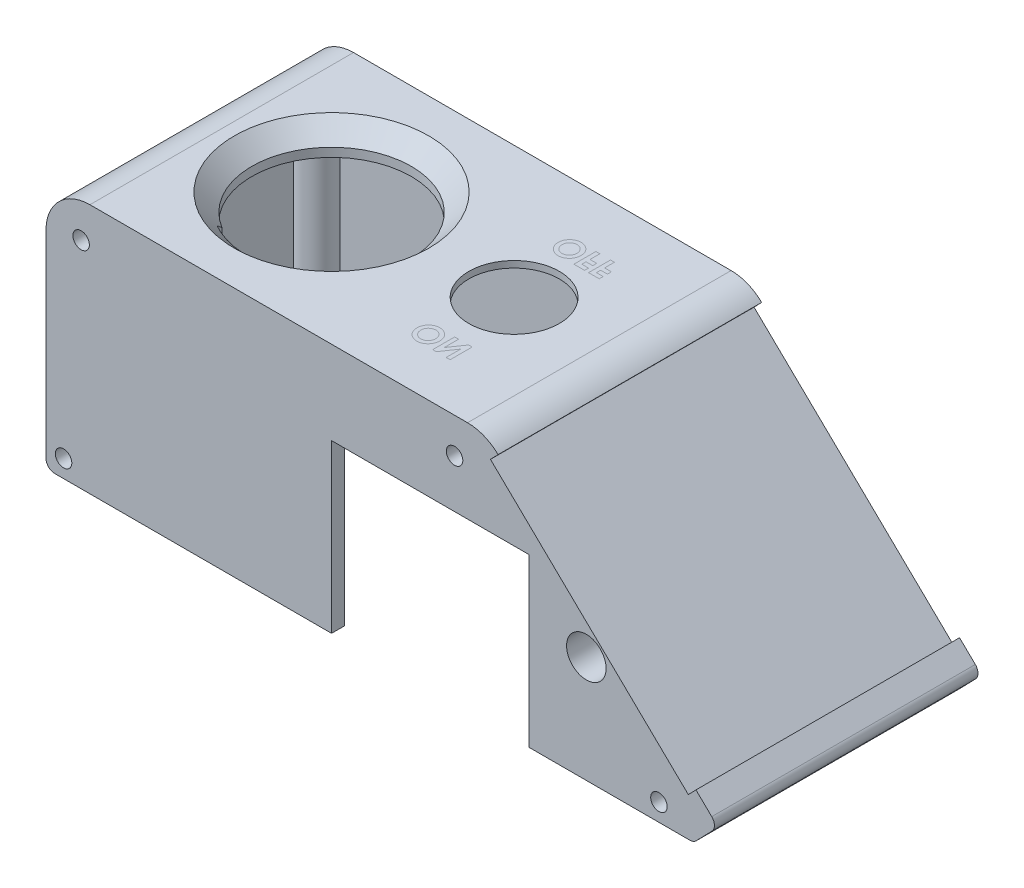
SolidWorks part; units mm, degrees
ref_plane "Plan de face" through (0, 0, 0) normal (0, 0, 1) x (1, 0, 0)
ref_plane "Plan de dessus" through (0, 0, 0) normal (0, 1, 0) x (1, 0, 0)
ref_plane "Plan de droite" through (0, 0, 0) normal (1, 0, 0) x (0, 0, -1)
sketch "Esquisse1" plane through (0, 0, 0) normal (0, 0, 1) x (1, 0, 0)
  line L0 (-123, 32.6826) -> (-123, -24.3174)
  line L1 (-123, -24.3174) -> (35.9266, -24.3174) construction
  line L2 (35.9266, -24.3174) -> (-23, 32.6826) construction
  line L3 (-23, 32.6826) -> (-123, 32.6826)
  line L4 (35.9266, -24.3174) -> (63.25, -50.7474) construction
  line L5 (63.25, -50.7474) -> (-123, -50.7474) construction
  line L6 (-123, -50.7474) -> (-123, -24.3174) construction
  line L7 (60.2885, -58.3174) -> (0, 0) construction
  line L8 (29.9822, -18.5673) -> (24.4201, -24.3174)
  line L9 (-123, -24.3174) -> (24.4201, -24.3174)
  line L10 (29.9822, -18.5673) -> (-23, 32.6826)
  circle A0 centre (0, 0) radius 4.5
  point P6 (49.5883, -37.5324)
  point P12 (60.2885, -58.3174)
  dimension "D8" = 9
  dimension "D1" = 83.43
  dimension "D2" = 57
  dimension "D3" = 100
  dimension "D4" = 186.25
  dimension "D5" = 7.5
  dimension "D6" = 91
  dimension "D7" = 123
  dimension "D9" = 8
extrude "Boss.-Extru.1" add sketch "Esquisse1" along normal blind 60
fillet "Congé2" radius 10 2 edges at (-123, 32.6826, 30) (-23, 32.6826, 30)
fillet "Congé4" radius 2 3 edges at (24.4201, -24.3174, 30) (29.9822, -18.5673, 30) (-123, -24.3174, 30)
sketch "Esquisse2" plane through (0, 0, 60) normal (0, 0, 1) x (1, 0, 0)
  line L2 (37.3481, -29.8662) -> (8.9506, -2.3972) construction
  line L3 (-27.0451, 29.6826) -> (-113, 29.6826)
  line L4 (-120, 22.6826) -> (-120, -21.3174)
  line L5 (-121, -24.3174) -> (23.5722, -24.3174)
  line L6 (25.0097, -23.7079) -> (28.5917, -20.0048)
  line L7 (28.5447, -17.1768) -> (-20.0925, 29.8702)
  line L8 (-27.0451, 32.6826) -> (-113, 32.6826)
  line L9 (-123, 22.6826) -> (-123, -22.3174)
  line L10 (-121, -24.3174) -> (23.5722, -24.3174) construction
  line L11 (25.0097, -23.7079) -> (28.5917, -20.0048) construction
  line L12 (28.5447, -17.1768) -> (-20.0925, 29.8702) construction
  line L13 (-27.0451, 32.6826) -> (-113, 32.6826) construction
  line L14 (-123, 22.6826) -> (-123, -22.3174) construction
  line L15 (-6.1095, 5.9097) -> (-4.3495, 7.7291)
  line L16 (6.1095, -5.9097) -> (7.8694, -4.0903)
  line L17 (-2.6933, 8.866) -> (-22.1783, 27.714) construction
  line L18 (25.7402, -18.6378) -> (-22.1783, 27.714) construction
  line L19 (-120, -21.3174) -> (-120, -24.3174)
  line L20 (-120, -24.3174) -> (23.1482, -24.3174)
  line L21 (23.1482, -24.3174) -> (23.1482, -21.3174)
  line L22 (23.1482, -21.3174) -> (23.1482, -18.8696)
  line L23 (-27.0451, 29.6826) -> (-4.3495, 7.7291)
  line L24 (-120, -21.3174) -> (23.1482, -21.3174) construction
  line L25 (7.8694, -4.0903) -> (23.1482, -18.8696)
  line L28 (23.1482, -21.3174) -> (25.7402, -18.6378) construction
  arc A0 (23.1482, -21.3174) -> (23.1482, -21.3174) centre (23.1482, -21.3174) ccw
  arc A1 (25.7402, -18.6378) -> (25.7402, -18.6378) centre (25.7402, -18.6378) ccw
  arc A2 (-22.1783, 27.714) -> (-27.0451, 29.6826) centre (-27.0451, 22.6826) ccw construction
  arc A3 (-113, 29.6826) -> (-120, 22.6826) centre (-113, 22.6826) ccw
  arc A4 (-120, -21.3174) -> (-120, -21.3174) centre (-120, -21.3174) ccw
  arc A5 (23.5722, -24.3174) -> (25.0097, -23.7079) centre (23.5722, -22.3174) ccw
  arc A6 (28.5917, -20.0048) -> (28.5447, -17.1768) centre (27.1542, -18.6143) ccw
  arc A7 (-20.0925, 29.8702) -> (-27.0451, 32.6826) centre (-27.0451, 22.6826) ccw
  arc A8 (-113, 32.6826) -> (-123, 22.6826) centre (-113, 22.6826) ccw
  arc A9 (-123, -22.3174) -> (-121, -24.3174) centre (-121, -22.3174) ccw
  arc A10 (23.5722, -24.3174) -> (25.0097, -23.7079) centre (23.5722, -22.3174) ccw construction
  arc A11 (28.5917, -20.0048) -> (28.5447, -17.1768) centre (27.1542, -18.6143) ccw construction
  arc A12 (-20.0925, 29.8702) -> (-27.0451, 32.6826) centre (-27.0451, 22.6826) ccw construction
  arc A13 (-113, 32.6826) -> (-123, 22.6826) centre (-113, 22.6826) ccw construction
  arc A14 (-123, -22.3174) -> (-121, -24.3174) centre (-121, -22.3174) ccw construction
  arc A15 (-6.1095, 5.9097) -> (6.1095, -5.9097) centre (0, 0) ccw
  circle A16 centre (0, 0) radius 4.5 construction
  line M15 (-121, -24.3174) -> (23.5722, -24.3174)
  dimension "D3" = 4
  dimension "D1" = 0
  dimension "D2" = 3
extrude "Enlèv. mat.-Extru.1" cut sketch "Esquisse2" against normal offset from surface (54 mm away) 3 from offset 3 contours A15 L15 L17 A2 L3 A3 L4 L19 L21 L22 L2 L16 M15 region at (-59.9986, 0.6696, 60) up to face at (-42.2983, -1.1726, 0) offset against normal yes
sketch "Esquisse3" plane through (0, 32.6826, 0) normal (0, 1, 0) x (1, 0, 0)
  line L0 (-88, -30) -> (-88, 0) construction
  line L1 (-27.0451, 0) -> (-113, 0) construction
  line L2 (-88, -30) -> (-88, -60) construction
  line L3 (-27.0451, -60) -> (-113, -60) construction
  line L4 (-88, -30) -> (-123, -30) construction
  line L5 (-123, -60) -> (-123, 0) construction
  line L6 (-97.43, -50) -> (-78.57, -50) construction
  circle A0 centre (-88, -30) radius 17.85
  circle A1 centre (-97.43, -50) radius 1.6
  circle A2 centre (-78.57, -50) radius 1.6
  point P15 (-88, -50)
  dimension "D1" = 35.7
  dimension "D3" = 3.2
  dimension "D4" = 20
  dimension "D2" = 35
  dimension "D5" = 18.86
sketch "Esquisse4" plane through (0, 32.6826, 0) normal (0, 1, 0) x (1, 0, 0)
  line L3 (-27.0451, 0) -> (-113, 0) construction
  line L5 (-113, 0) -> (-113, -60)
  line L6 (-123, -60) -> (-113, -60) construction
  line L7 (-113, -60) -> (-97.43, -60)
  line L8 (-27.0451, -60) -> (-113, -60) construction
  line L9 (-65.85, -60) -> (-65.85, 0)
  line L10 (-65.85, 0) -> (-113, 0)
  line L12 (-113, 0) -> (-113, -60) construction
  line L13 (-97.43, -47.5) -> (-97.43, -45.508)
  line L14 (-97.43, -52.5) -> (-97.43, -60)
  line L15 (-78.57, -52.5) -> (-78.57, -60)
  line L16 (-78.57, -47.5) -> (-78.57, -45.508)
  line L17 (-78.57, -60) -> (-65.85, -60)
  circle A0 centre (-97.43, -50) radius 1.675
  circle A1 centre (-78.57, -50) radius 1.675
  arc A2 (-97.43, -52.5) -> (-97.43, -47.5) centre (-97.43, -50) ccw
  arc A5 (-78.57, -47.5) -> (-78.57, -52.5) centre (-78.57, -50) ccw
  arc A6 (-78.57, -45.508) -> (-97.43, -45.508) centre (-88, -30) ccw
  point P9 (-69.85, -30)
  dimension "D1" = 3.35
  dimension "D2" = 5
  dimension "D3" = 5
  dimension "D4" = 36.3
  dimension "D5" = 4
extrude "Boss.-Extru.2" add sketch "Esquisse4" against normal blind 6
sketch "Esquisse5" plane through (-113, 0, 0) normal (-1, 0, 0) x (0, 0, 1)
  line L4 (57, 26.6826) -> (57, 29.6826)
  line L5 (57, 29.6826) -> (3, 29.6826)
  line L6 (3, 29.6826) -> (3, 26.6826)
  line L7 (3, 26.6826) -> (57, 26.6826)
  line L8 (57, 26.6826) -> (57, 29.6826)
  line L9 (57, 29.6826) -> (3, 29.6826)
  line L10 (3, 29.6826) -> (3, 26.6826)
  line L11 (3, 26.6826) -> (57, 26.6826)
  dimension "D1" = 0
extrude "Boss.-Extru.3" add sketch "Esquisse5" along normal up to next
sketch "Esquisse6" plane through (0, 32.6826, 0) normal (0, 1, 0) x (1, 0, 0)
  circle A3 centre (-88, -30) radius 18.15
  arc A4 (-78.57, -45.508) -> (-97.43, -45.508) centre (-88, -30) ccw construction
extrude "Enlèv. mat.-Extru.2" cut sketch "Esquisse6" against normal through all
chamfer "Chanfrein1" distance 4 angle 45 1 edges at (-106.15, 32.6826, 30)
chamfer "Chanfrein2" distance 3 distance2 3 1 edges at (-65.85, 26.6826, 30)
fillet "Congé5" radius 1 6 edges at (-78.57, 28.1826, 47.5) (-78.57, 28.1826, 52.5) (-97.43, 28.1826, 52.5) (-97.43, 28.1826, 47.5) (-97.43, 28.1826, 57) (-78.57, 28.1826, 57)
sketch "Esquisse7" plane through (0, 32.6826, 0) normal (0, 1, 0) x (1, 0, 0)
  line L0 (-51.5128, -13.5025) -> (-51.5128, -47.5732) construction
  text T0 "<b>TEST</b>" font "Century Gothic" height 5
  text T1 "     <b> TEST</b>" font "Century Gothic" height 7
extrude "Enlèv. mat.-Extru.3" [suppressed] cut sketch "Esquisse7" against normal blind 0.2
sketch "Esquisse8" plane through (0, 32.6826, 0) normal (0, 1, 0) x (1, 0, 0)
  line L1 (-101.3359, -3.489) -> (-40.5469, -3.489)
  line L2 (-101.3359, -3.489) -> (-101.3359, -57)
  line L3 (-101.3359, -57) -> (-40.5469, -57)
  line L4 (-40.5469, -3.489) -> (-40.5469, -57)
  line L5 (-27.0451, -57) -> (-65.85, -57) construction
extrude "Enlèv. mat.-Extru.4" [suppressed] cut sketch "Esquisse8" against normal through all flip side to cut
sketch "Esquisse12" [suppressed] plane through (0, 26.4324, 0) normal (0, 1, 0) x (1, 0, 0)
  line L0 (-44.5128, -43.8359) -> (-45.7692, -43.8359) construction
  line L1 (-45.7692, -43.8359) -> (-45.7692, -45.0923) construction
  line L2 (-45.7692, -45.0923) -> (-51.5128, -45.0923) construction
  line L3 (-51.5128, -45.0923) -> (-51.5128, -46.3487) construction
  line L4 (-51.5128, -46.3487) -> (-45.7692, -46.3487) construction
  line L5 (-45.7692, -46.3487) -> (-45.7692, -47.6051) construction
  line L6 (-45.7692, -47.6051) -> (-44.5128, -47.6051) construction
  line L7 (-44.5128, -47.6051) -> (-44.5128, -43.8359) construction
  line L8 (-49.5384, -40.0947) -> (-50.2017, -38.9897) construction
  line L9 (-46.3076, -42.1784) -> (-45.4481, -43.1179) construction
  line L10 (-44.5128, -34.5025) -> (-51.5128, -34.5025) construction
  line L11 (-51.5128, -34.5025) -> (-51.5128, -38.2718) construction
  line L12 (-51.5128, -38.2718) -> (-50.2564, -38.2718) construction
  line L13 (-50.2564, -38.2718) -> (-50.2564, -35.7589) construction
  line L14 (-50.2564, -35.7589) -> (-48.3717, -35.7589) construction
  line L15 (-48.3717, -35.7589) -> (-48.3717, -38.2718) construction
  line L16 (-48.3717, -38.2718) -> (-47.1153, -38.2718) construction
  line L17 (-47.1153, -38.2718) -> (-47.1153, -35.7589) construction
  line L18 (-47.1153, -35.7589) -> (-45.7692, -35.7589) construction
  line L19 (-45.7692, -35.7589) -> (-45.7692, -38.2718) construction
  line L20 (-45.7692, -38.2718) -> (-44.5128, -38.2718) construction
  line L21 (-44.5128, -38.2718) -> (-44.5128, -34.5025) construction
  line L22 (-44.5128, -29.7461) -> (-45.7692, -29.7461) construction
  line L23 (-45.7692, -29.7461) -> (-45.7692, -31.0025) construction
  line L24 (-45.7692, -31.0025) -> (-51.5128, -31.0025) construction
  line L25 (-51.5128, -31.0025) -> (-51.5128, -32.2589) construction
  line L26 (-51.5128, -32.2589) -> (-45.7692, -32.2589) construction
  line L27 (-45.7692, -32.2589) -> (-45.7692, -33.5153) construction
  line L28 (-45.7692, -33.5153) -> (-44.5128, -33.5153) construction
  line L29 (-44.5128, -33.5153) -> (-44.5128, -29.7461) construction
  line L30 (-46.5128, -23.6307) -> (-47.4102, -23.6307) construction
  line L31 (-47.4102, -23.6307) -> (-47.4102, -24.5282) construction
  line L32 (-47.4102, -24.5282) -> (-51.5128, -24.5282) construction
  line L33 (-51.5128, -24.5282) -> (-51.5128, -25.4256) construction
  line L34 (-51.5128, -25.4256) -> (-47.4102, -25.4256) construction
  line L35 (-47.4102, -25.4256) -> (-47.4102, -26.323) construction
  line L36 (-47.4102, -26.323) -> (-46.5128, -26.323) construction
  line L37 (-46.5128, -26.323) -> (-46.5128, -23.6307) construction
  line L38 (-50.1025, -20.9585) -> (-50.5763, -20.1692) construction
  line L39 (-47.7948, -22.4468) -> (-47.1808, -23.1179) construction
  line L40 (-46.5128, -16.9641) -> (-51.5128, -16.9641) construction
  line L41 (-51.5128, -16.9641) -> (-51.5128, -19.6564) construction
  line L42 (-51.5128, -19.6564) -> (-50.6153, -19.6564) construction
  line L43 (-50.6153, -19.6564) -> (-50.6153, -17.8615) construction
  line L44 (-50.6153, -17.8615) -> (-49.2692, -17.8615) construction
  line L45 (-49.2692, -17.8615) -> (-49.2692, -19.6564) construction
  line L46 (-49.2692, -19.6564) -> (-48.3717, -19.6564) construction
  line L47 (-48.3717, -19.6564) -> (-48.3717, -17.8615) construction
  line L48 (-48.3717, -17.8615) -> (-47.4102, -17.8615) construction
  line L49 (-47.4102, -17.8615) -> (-47.4102, -19.6564) construction
  line L50 (-47.4102, -19.6564) -> (-46.5128, -19.6564) construction
  line L51 (-46.5128, -19.6564) -> (-46.5128, -16.9641) construction
  line L52 (-46.5128, -13.5666) -> (-47.4102, -13.5666) construction
  line L53 (-47.4102, -13.5666) -> (-47.4102, -14.4641) construction
  line L54 (-47.4102, -14.4641) -> (-51.5128, -14.4641) construction
  line L55 (-51.5128, -14.4641) -> (-51.5128, -15.3615) construction
  line L56 (-51.5128, -15.3615) -> (-47.4102, -15.3615) construction
  line L57 (-47.4102, -15.3615) -> (-47.4102, -16.2589) construction
  line L58 (-47.4102, -16.2589) -> (-46.5128, -16.2589) construction
  line L59 (-46.5128, -16.2589) -> (-46.5128, -13.5666) construction
  line L60 (-44.5128, -43.8359) -> (-45.7692, -43.8359)
  line L61 (-45.7692, -43.8359) -> (-45.7692, -45.0923)
  line L62 (-45.7692, -45.0923) -> (-51.5128, -45.0923)
  line L63 (-51.5128, -45.0923) -> (-51.5128, -46.3487)
  line L64 (-51.5128, -46.3487) -> (-45.7692, -46.3487)
  line L65 (-45.7692, -46.3487) -> (-45.7692, -47.6051)
  line L66 (-45.7692, -47.6051) -> (-44.5128, -47.6051)
  line L67 (-44.5128, -47.6051) -> (-44.5128, -43.8359)
  line L68 (-49.5384, -40.0947) -> (-50.2017, -38.9897)
  line L69 (-46.3076, -42.1784) -> (-45.4481, -43.1179)
  line L70 (-44.5128, -34.5025) -> (-51.5128, -34.5025)
  line L71 (-51.5128, -34.5025) -> (-51.5128, -38.2718)
  line L72 (-51.5128, -38.2718) -> (-50.2564, -38.2718)
  line L73 (-50.2564, -38.2718) -> (-50.2564, -35.7589)
  line L74 (-50.2564, -35.7589) -> (-48.3717, -35.7589)
  line L75 (-48.3717, -35.7589) -> (-48.3717, -38.2718)
  line L76 (-48.3717, -38.2718) -> (-47.1153, -38.2718)
  line L77 (-47.1153, -38.2718) -> (-47.1153, -35.7589)
  line L78 (-47.1153, -35.7589) -> (-45.7692, -35.7589)
  line L79 (-45.7692, -35.7589) -> (-45.7692, -38.2718)
  line L80 (-45.7692, -38.2718) -> (-44.5128, -38.2718)
  line L81 (-44.5128, -38.2718) -> (-44.5128, -34.5025)
  line L82 (-44.5128, -29.7461) -> (-45.7692, -29.7461)
  line L83 (-45.7692, -29.7461) -> (-45.7692, -31.0025)
  line L84 (-45.7692, -31.0025) -> (-51.5128, -31.0025)
  line L85 (-51.5128, -31.0025) -> (-51.5128, -32.2589)
  line L86 (-51.5128, -32.2589) -> (-45.7692, -32.2589)
  line L87 (-45.7692, -32.2589) -> (-45.7692, -33.5153)
  line L88 (-45.7692, -33.5153) -> (-44.5128, -33.5153)
  line L89 (-44.5128, -33.5153) -> (-44.5128, -29.7461)
  line L90 (-46.5128, -23.6307) -> (-47.4102, -23.6307)
  line L91 (-47.4102, -23.6307) -> (-47.4102, -24.5282)
  line L92 (-47.4102, -24.5282) -> (-51.5128, -24.5282)
  line L93 (-51.5128, -24.5282) -> (-51.5128, -25.4256)
  line L94 (-51.5128, -25.4256) -> (-47.4102, -25.4256)
  line L95 (-47.4102, -25.4256) -> (-47.4102, -26.323)
  line L96 (-47.4102, -26.323) -> (-46.5128, -26.323)
  line L97 (-46.5128, -26.323) -> (-46.5128, -23.6307)
  line L98 (-50.1025, -20.9585) -> (-50.5763, -20.1692)
  line L99 (-47.7948, -22.4468) -> (-47.1808, -23.1179)
  line L100 (-46.5128, -16.9641) -> (-51.5128, -16.9641)
  line L101 (-51.5128, -16.9641) -> (-51.5128, -19.6564)
  line L102 (-51.5128, -19.6564) -> (-50.6153, -19.6564)
  line L103 (-50.6153, -19.6564) -> (-50.6153, -17.8615)
  line L104 (-50.6153, -17.8615) -> (-49.2692, -17.8615)
  line L105 (-49.2692, -17.8615) -> (-49.2692, -19.6564)
  line L106 (-49.2692, -19.6564) -> (-48.3717, -19.6564)
  line L107 (-48.3717, -19.6564) -> (-48.3717, -17.8615)
  line L108 (-48.3717, -17.8615) -> (-47.4102, -17.8615)
  line L109 (-47.4102, -17.8615) -> (-47.4102, -19.6564)
  line L110 (-47.4102, -19.6564) -> (-46.5128, -19.6564)
  line L111 (-46.5128, -19.6564) -> (-46.5128, -16.9641)
  line L112 (-46.5128, -13.5666) -> (-47.4102, -13.5666)
  line L113 (-47.4102, -13.5666) -> (-47.4102, -14.4641)
  line L114 (-47.4102, -14.4641) -> (-51.5128, -14.4641)
  line L115 (-51.5128, -14.4641) -> (-51.5128, -15.3615)
  line L116 (-51.5128, -15.3615) -> (-47.4102, -15.3615)
  line L117 (-47.4102, -15.3615) -> (-47.4102, -16.2589)
  line L118 (-47.4102, -16.2589) -> (-46.5128, -16.2589)
  line L119 (-46.5128, -16.2589) -> (-46.5128, -13.5666)
  spline S0 degree 3 poles (2576.1231, -3063.9638) (-78.978, -31.5994) (-51.7602, -48.9954) (-45.1575, -42.8617) (-45.0281, -42.7366) (-44.9129, -42.6128) (-44.8093, -42.4912) (-44.7182, -42.3725) (-44.6392, -42.2561) (-44.5515, -42.1048) (-44.4637, -41.9128) (-44.3892, -41.6754) (-43.0007, -34.4786) (-90.3377, -22.6052) (3938.4648, -408.9571) knots -11.439326 -11.439326 -11.439326 -11.439326 0.086863 0.16924 0.246406 0.320182 0.388569 0.453439 0.514138 0.570911 0.680237 0.787033 0.893094 10.151041 10.151041 10.151041 10.151041 only from (-45.4481, -43.1179) to (-44.3333, -41.1856) construction
  spline S1 degree 3 poles (3948.4966, 193.9155) (-81.7616, -56.9875) (-43.4592, -47.677) (-44.3624, -40.8134) (-44.4032, -40.6372) (-44.4601, -40.4686) (-44.5358, -40.3091) (-44.6258, -40.1565) (-44.7327, -40.012) (-44.8546, -39.8771) (-44.9857, -39.7528) (-45.1274, -39.6456) (-45.275, -39.5545) (-45.4282, -39.4774) (-45.5895, -39.4199) (-45.7569, -39.3798) (-51.9341, -38.4317) (-61.2475, -78.4637) (246.5205, 3949.6346) knots -7.093144 -7.093144 -7.093144 -7.093144 0.067126 0.131773 0.195047 0.257576 0.31912 0.381022 0.44414 0.50839 0.572579 0.634512 0.695405 0.755386 0.815123 0.875519 0.936815 7.39287 7.39287 7.39287 7.39287 only from (-44.3333, -41.1856) to (-46.1085, -39.3487) construction
  spline S2 degree 3 poles (-546.3124, 3928.9112) (-26.4308, -90.3374) (-40.038, -37.7186) (-46.6204, -39.426) (-46.8767, -39.5277) (-47.0886, -39.6476) (-47.2634, -39.7717) (-47.4107, -39.8898) (-47.5699, -40.034) (-47.7441, -40.2011) (-47.9317, -40.3933) (-48.1315, -40.6109) (-59.538, -53.5136) (-49.387, -84.849) (-3112.2335, 2530.0691) knots -6.240778 -6.240778 -6.240778 -6.240778 0.081082 0.164737 0.252219 0.345525 0.397733 0.458121 0.526821 0.604004 0.690069 0.784779 0.887865 17.235784 17.235784 17.235784 17.235784 only from (-46.1085, -39.3487) to (-48.5652, -41.1127) construction
  spline S3 degree 3 poles (3015.2327, -2612.2581) (-49.6318, -9.685) (-41.0131, -32.4999) (-48.7917, -41.376) (-48.8953, -41.4893) (-48.9906, -41.5903) (-49.0774, -41.6794) (-49.1573, -41.7547) (-49.2281, -41.8183) (-49.3111, -41.8832) (-49.4107, -41.9454) (-49.5308, -41.9996) (-53.4169, -43.1068) (-63.4762, -1.8452) (519.3936, -4001.0463) knots -22.252785 -22.252785 -22.252785 -22.252785 0.117351 0.224428 0.322528 0.411079 0.490114 0.56032 0.621135 0.672109 0.761675 0.844926 0.923662 8.43466 8.43466 8.43466 8.43466 only from (-48.5652, -41.1127) to (-49.7726, -42.041) construction
  spline S4 degree 3 poles (-782.9235, -3974.1128) (-33.7441, 4.3084) (-46.4991, -43.3471) (-50.0233, -41.9864) (-50.1378, -41.9135) (-50.2393, -41.8119) (-50.3283, -41.6922) (-50.3895, -41.553) (-51.6411, -36.8097) (-5.0943, -25.7896) (-4017.6128, -552.1083) knots -9.388494 -9.388494 -9.388494 -9.388494 0.11167 0.222033 0.33776 0.463701 0.594726 0.724651 0.858078 13.313493 13.313493 13.313493 13.313493 only from (-49.7726, -42.041) to (-50.4358, -41.2417) construction
  spline S5 degree 3 poles (-4014.0912, 495.3159) (-5.5802, -56.8515) (-51.7029, -45.6194) (-50.3834, -40.9231) (-50.3119, -40.771) (-50.2118, -40.6242) (-50.0844, -40.482) (-49.9279, -40.3462) (-43.3747, -35.5914) (-13.7099, -67.4698) (-2169.156, 3351.9171) knots -9.178113 -9.178113 -9.178113 -9.178113 0.104971 0.210442 0.318778 0.433771 0.557861 0.692388 0.839542 16.419544 16.419544 16.419544 16.419544 only from (-50.4358, -41.2417) to (-49.5384, -40.0947) construction
  spline S6 degree 3 poles (-1921.8477, 3495.9204) (-19.4681, -58.3713) (-42.6588, -34.5068) (-50.5608, -39.1895) (-50.7208, -39.3001) (-50.8703, -39.4125) (-51.0048, -39.5325) (-51.1279, -39.6559) (-51.2371, -39.7852) (-51.3349, -39.9188) (-51.4191, -40.0585) (-51.4923, -40.2033) (-51.5545, -40.3542) (-51.6044, -40.5109) (-51.6442, -40.6735) (-51.6719, -40.8422) (-52.3816, -48.0616) (-18.1191, -56.9381) (-4047.6242, 133.426) knots -9.530009 -9.530009 -9.530009 -9.530009 0.074827 0.146497 0.215054 0.281265 0.344905 0.406322 0.466185 0.52446 0.581915 0.639182 0.696602 0.754991 0.813735 0.874115 0.93644 8.508421 8.508421 8.508421 8.508421 only from (-50.2017, -38.9897) to (-51.6923, -41.1954) construction
  spline S7 degree 3 poles (-4045.5645, -258.3907) (-11.6165, -23.7536) (-52.6279, -33.9218) (-51.6606, -41.6397) (-51.6163, -41.8472) (-51.5538, -42.0437) (-51.4761, -42.2296) (-51.3779, -42.4036) (-51.2626, -42.5664) (-51.1315, -42.7177) (-50.9855, -42.8525) (-50.8314, -42.9738) (-50.6648, -43.073) (-50.4898, -43.1544) (-50.3063, -43.2206) (-50.1121, -43.2636) (-43.2575, -44.28) (-33.1765, -1.5429) (-329.7968, -4033.245) knots -6.962823 -6.962823 -6.962823 -6.962823 0.070366 0.137733 0.203055 0.265952 0.32781 0.388651 0.449934 0.5117 0.573052 0.633022 0.692432 0.751488 0.810977 0.87209 0.934807 7.193918 7.193918 7.193918 7.193918 only from (-51.6923, -41.1954) to (-49.6997, -43.2974) construction
  spline S8 degree 3 poles (203.1413, -4035.086) (-66.4147, -2.0825) (-56.3938, -44.3175) (-49.2734, -43.2609) (-49.0721, -43.2081) (-48.8764, -43.1359) (-48.6829, -43.0374) (-48.4892, -42.9086) (-41.2083, -37.2922) (-61.5956, 0.4302) (2577.7506, -3059.6673) knots -11.54118 -11.54118 -11.54118 -11.54118 0.120155 0.237559 0.351197 0.464403 0.582502 0.710089 0.849189 15.799983 15.799983 15.799983 15.799983 only from (-49.6997, -43.2974) to (-48.0941, -42.5738) construction
  spline S9 degree 3 poles (2793.2527, -2857.2663) (-67.8993, -38.4732) (-51.8188, -46.501) (-47.9754, -42.4522) (-47.8961, -42.3675) (-47.8027, -42.2641) (-47.6948, -42.1416) (-47.5713, -42.0018) (-25.4331, -16.3594) (3.6462, 3.0536) (-2973.2275, 2684.1488) knots -13.60128 -13.60128 -13.60128 -13.60128 0.057325 0.134323 0.229376 0.344988 0.479543 0.633816 0.807047 84.417644 84.417644 84.417644 84.417644 only from (-48.0941, -42.5738) to (-47.2864, -41.6722) construction
  spline S10 degree 3 poles (-3076.286, 2570.2751) (-57.3613, -81.0661) (-59.2038, -55.0029) (-46.9756, -41.3212) (-46.8407, -41.1715) (-46.7207, -41.0428) (-46.6148, -40.934) (-46.5246, -40.8452) (-43.491, -37.9568) (-23.4564, -54.9268) (-2643.1224, 3001.2568) knots -41.42479 -41.42479 -41.42479 -41.42479 0.190755 0.364029 0.516815 0.65136 0.766197 0.863652 0.940766 10.331147 10.331147 10.331147 10.331147 only from (-47.2864, -41.6722) to (-46.3834, -40.7215) construction
  spline S11 degree 3 poles (-2017.617, 3439.5558) (-34.196, -76.3756) (-49.4928, -42.0441) (-46.222, -40.6329) (-43.1404, -39.7709) (-34.592, -77.62) (-599.24, 3920.7535) knots -28.750782 -28.750782 -28.750782 -28.750782 0.262162 0.512885 0.758119 26.702092 26.702092 26.702092 26.702092 only from (-46.3834, -40.7215) to (-46.0482, -40.6051) construction
  spline S12 degree 3 poles (582.5043, 3909.4982) (-58.1332, -79.5254) (-48.7193, -39.6223) (-45.877, -40.6413) (-45.8005, -40.6951) (-45.7275, -40.7625) (-45.6669, -40.8475) (-45.6206, -40.945) (-44.658, -44.8818) (-85.886, -53.2117) (3933.5685, 364.7019) knots -10.722382 -10.722382 -10.722382 -10.722382 0.106734 0.215599 0.328417 0.45262 0.583366 0.714007 0.851874 15.527175 15.527175 15.527175 15.527175 only from (-46.0482, -40.6051) to (-45.5897, -41.1716) construction
  spline S13 degree 3 poles (3915.3484, -597.729) (-86.8427, -27.103) (-44.497, -37.3654) (-45.6324, -41.4303) (-45.6885, -41.5586) (-45.7698, -41.6846) (-45.8708, -41.811) (-45.996, -41.9356) (-51.722, -46.8578) (-81.3339, -20.6312) (2374.8716, -3225.9965) knots -9.47701 -9.47701 -9.47701 -9.47701 0.099714 0.202442 0.310946 0.425725 0.551534 0.688152 0.837568 18.163614 18.163614 18.163614 18.163614 only from (-45.5897, -41.1716) to (-46.3076, -42.1784) construction
  spline S14 degree 3 poles (2578.3841, -3040.4547) (-75.8798, -11.7546) (-52.2375, -27.8251) (-46.9733, -22.9349) (-46.8809, -22.8456) (-46.7985, -22.7571) (-46.7246, -22.6703) (-46.6595, -22.5855) (-46.6031, -22.5024) (-46.5404, -22.3942) (-46.4777, -22.2571) (-46.4245, -22.0875) (-45.319, -16.3575) (-87.5554, -6.4531) (3936.0777, -393.7474) knots -12.796916 -12.796916 -12.796916 -12.796916 0.086863 0.16924 0.246406 0.320182 0.388569 0.453439 0.514138 0.570911 0.680237 0.787033 0.893094 11.237014 11.237014 11.237014 11.237014 only from (-47.1808, -23.1179) to (-46.3846, -21.7377) construction
  spline S15 degree 3 poles (3946.2554, 217.412) (-79.8747, -34.5988) (-45.6857, -26.9407) (-46.4054, -21.4718) (-46.4345, -21.346) (-46.4752, -21.2256) (-46.5293, -21.1116) (-46.5935, -21.0026) (-46.6699, -20.8994) (-46.7569, -20.8031) (-46.8506, -20.7142) (-46.9518, -20.6377) (-47.0572, -20.5726) (-47.1667, -20.5175) (-47.2818, -20.4764) (-47.4014, -20.4479) (-52.3226, -19.6925) (-60.0458, -55.4184) (248.6157, 3968.2585) knots -7.934967 -7.934967 -7.934967 -7.934967 0.067126 0.131773 0.195047 0.257576 0.31912 0.381022 0.44414 0.50839 0.572579 0.634512 0.695405 0.755386 0.815123 0.875519 0.936815 8.151509 8.151509 8.151509 8.151509 only from (-46.3846, -21.7377) to (-47.6526, -20.4256) construction
  spline S16 degree 3 poles (-551.7519, 3947.4667) (-31.2816, -66.0556) (-42.7802, -19.1222) (-48.0182, -20.4809) (-48.2013, -20.5535) (-48.3526, -20.6391) (-48.4775, -20.7278) (-48.5827, -20.8121) (-48.6964, -20.9151) (-48.8208, -21.0345) (-48.9548, -21.1717) (-49.0976, -21.3272) (-58.1941, -31.6169) (-48.0848, -58.3515) (-3106.6104, 2557.3704) knots -6.981373 -6.981373 -6.981373 -6.981373 0.081082 0.164737 0.252219 0.345525 0.397733 0.458121 0.526821 0.604004 0.690069 0.784779 0.887865 19.16302 19.16302 19.16302 19.16302 only from (-47.6526, -20.4256) to (-49.4074, -21.6856) construction
  spline S17 degree 3 poles (3009.9058, -2598.2223) (-51.7774, 4.7305) (-43.3629, -14.7918) (-49.5691, -21.8737) (-49.6432, -21.9546) (-49.7112, -22.0268) (-49.7732, -22.0904) (-49.8303, -22.1442) (-49.8809, -22.1896) (-49.9402, -22.2359) (-50.0113, -22.2804) (-50.0971, -22.3191) (-53.192, -23.2009) (-61.7881, 13.6217) (521.1684, -3980.7198) knots -24.894053 -24.894053 -24.894053 -24.894053 0.117351 0.224428 0.322528 0.411079 0.490114 0.56032 0.621135 0.672109 0.761675 0.844926 0.923662 9.316723 9.316723 9.316723 9.316723 only from (-49.4074, -21.6856) to (-50.2698, -22.3487) construction
  spline S18 degree 3 poles (-785.5131, -3953.8476) (-36.6199, 19.1189) (-47.6433, -23.3929) (-50.4489, -22.3097) (-50.5307, -22.2576) (-50.6032, -22.185) (-50.6667, -22.0996) (-50.7105, -22.0002) (-51.7071, -18.2229) (-10.18, -8.8527) (-4017.3746, -535.4374) knots -10.502405 -10.502405 -10.502405 -10.502405 0.11167 0.222033 0.33776 0.463701 0.594726 0.724651 0.858078 14.774469 14.774469 14.774469 14.774469 only from (-50.2698, -22.3487) to (-50.7435, -21.7778) construction
  spline S19 degree 3 poles (-4014.0327, 517.5719) (-10.6042, -34.8524) (-51.7566, -25.2894) (-50.7061, -21.5502) (-50.655, -21.4415) (-50.5835, -21.3367) (-50.4925, -21.2351) (-50.3807, -21.1381) (-45.1599, -17.3501) (-19.3562, -46.1643) (-2173.6955, 3368.4798) knots -10.26726 -10.26726 -10.26726 -10.26726 0.104971 0.210442 0.318778 0.433771 0.557861 0.692388 0.839542 18.249316 18.249316 18.249316 18.249316 only from (-50.7435, -21.7778) to (-50.1025, -20.9585) construction
  spline S20 degree 3 poles (-1926.9879, 3512.1796) (-24.6016, -38.2763) (-44.5334, -16.5789) (-50.8328, -20.3119) (-50.9471, -20.3909) (-51.0538, -20.4712) (-51.1499, -20.5569) (-51.2379, -20.645) (-51.3159, -20.7374) (-51.3857, -20.8328) (-51.4459, -20.9326) (-51.4981, -21.036) (-51.5425, -21.1438) (-51.5782, -21.2558) (-51.6067, -21.3719) (-51.6264, -21.4924) (-52.1921, -27.2463) (-21.6061, -34.4864) (-4047.5257, 157.1414) knots -10.661059 -10.661059 -10.661059 -10.661059 0.074827 0.146497 0.215054 0.281265 0.344905 0.406322 0.466185 0.52446 0.581915 0.639182 0.696602 0.754991 0.813735 0.874115 0.93644 9.399607 9.399607 9.399607 9.399607 only from (-50.5763, -20.1692) to (-51.641, -21.7447) construction
  spline S21 degree 3 poles (-4045.2886, -243.4813) (-15.7914, -7.5714) (-52.389, -15.9135) (-51.6184, -22.062) (-51.5867, -22.2103) (-51.5421, -22.3507) (-51.4866, -22.4834) (-51.4165, -22.6077) (-51.3341, -22.724) (-51.2404, -22.8321) (-51.1362, -22.9283) (-51.026, -23.0149) (-50.9071, -23.0858) (-50.7821, -23.144) (-50.651, -23.1913) (-50.5123, -23.222) (-45.0524, -24.0315) (-36.7094, 14.0985) (-334.3374, -4012.7648) knots -7.789142 -7.789142 -7.789142 -7.789142 0.070366 0.137733 0.203055 0.265952 0.32781 0.388651 0.449934 0.5117 0.573052 0.633022 0.692432 0.751488 0.810977 0.87209 0.934807 7.928861 7.928861 7.928861 7.928861 only from (-51.641, -21.7447) to (-50.2177, -23.2461) construction
  spline S22 degree 3 poles (206.814, -4014.7822) (-63.8503, 13.627) (-55.585, -24.0617) (-49.9132, -23.2201) (-49.7695, -23.1823) (-49.6297, -23.1308) (-49.4914, -23.0604) (-49.3531, -22.9684) (-43.5521, -18.4936) (-62.3722, 14.572) (2572.7887, -3043.4458) knots -12.910829 -12.910829 -12.910829 -12.910829 0.120155 0.237559 0.351197 0.464403 0.582502 0.710089 0.849189 17.556514 17.556514 17.556514 17.556514 only from (-50.2177, -23.2461) to (-49.0709, -22.7293) construction
  spline S23 degree 3 poles (2794.6323, -2835.0983) (-66.0383, -18.3335) (-52.0518, -25.8719) (-48.9861, -22.6424) (-48.9294, -22.5819) (-48.8627, -22.508) (-48.7857, -22.4205) (-48.6975, -22.3207) (-31.0176, -1.8424) (-7.1305, 13.08) (-2988.5385, 2689.1287) knots -15.215613 -15.215613 -15.215613 -15.215613 0.057325 0.134323 0.229376 0.344988 0.479543 0.633816 0.807047 94.326999 94.326999 94.326999 94.326999 only from (-49.0709, -22.7293) to (-48.4939, -22.0853) construction
  spline S24 degree 3 poles (-3070.4174, 2598.1882) (-55.2419, -54.728) (-58.0304, -32.7529) (-48.2719, -21.8345) (-48.1756, -21.7276) (-48.0898, -21.6357) (-48.0142, -21.558) (-47.9498, -21.4946) (-45.532, -19.1925) (-27.9578, -34.5827) (-2646.5522, 3019.0834) knots -46.34213 -46.34213 -46.34213 -46.34213 0.190755 0.364029 0.516815 0.65136 0.766197 0.863652 0.940766 11.438697 11.438697 11.438697 11.438697 only from (-48.4939, -22.0853) to (-47.8489, -21.4062) construction
  spline S25 degree 3 poles (-2017.2876, 3459.924) (-36.4157, -52.9116) (-50.34, -22.4674) (-47.7337, -21.3429) (-45.2786, -20.6562) (-37.9511, -54.434) (-602.6302, 3939.6922) knots -32.16282 -32.16282 -32.16282 -32.16282 0.262162 0.512885 0.758119 29.752008 29.752008 29.752008 29.752008 only from (-47.8489, -21.4062) to (-47.6095, -21.323) construction
  spline S26 degree 3 poles (582.658, 3928.5098) (-57.87, -56.1504) (-49.7512, -20.5372) (-47.4872, -21.3489) (-47.4326, -21.3873) (-47.3804, -21.4355) (-47.3372, -21.4962) (-47.3041, -21.5658) (-46.5371, -24.7023) (-83.3281, -31.7556) (3931.6701, 386.4905) knots -11.994858 -11.994858 -11.994858 -11.994858 0.106734 0.215599 0.328417 0.45262 0.583366 0.714007 0.851874 17.251222 17.251222 17.251222 17.251222 only from (-47.6095, -21.323) to (-47.282, -21.7277) construction
  spline S27 degree 3 poles (3913.2041, -580.6881) (-84.1954, -9.9153) (-46.4083, -18.6754) (-47.3125, -21.9125) (-47.3526, -22.0041) (-47.4107, -22.0941) (-47.4828, -22.1844) (-47.5723, -22.2734) (-52.1353, -26.1959) (-77.9765, -2.3871) (2376.9133, -3203.5876) knots -10.601536 -10.601536 -10.601536 -10.601536 0.099714 0.202442 0.310946 0.425725 0.551534 0.688152 0.837568 20.200514 20.200514 20.200514 20.200514 only from (-47.282, -21.7277) to (-47.7948, -22.4468) construction
  spline S28 degree 3 poles (-45.4481, -43.1179) (-45.3967, -43.0749) (-45.2967, -42.991) (-45.1575, -42.8617) (-45.0281, -42.7366) (-44.9129, -42.6128) (-44.8093, -42.4912) (-44.7182, -42.3725) (-44.6392, -42.2561) (-44.5515, -42.1048) (-44.4637, -41.9128) (-44.3892, -41.6754) (-44.3423, -41.4324) (-44.3363, -41.2681) (-44.3333, -41.1856) knots 0 0 0 0 0.086863 0.16924 0.246406 0.320182 0.388569 0.453439 0.514138 0.570911 0.680237 0.787033 0.893094 1 1 1 1
  spline S29 degree 3 poles (-44.3333, -41.1856) (-44.335, -41.122) (-44.3382, -40.997) (-44.3624, -40.8134) (-44.4032, -40.6372) (-44.4601, -40.4686) (-44.5358, -40.3091) (-44.6258, -40.1565) (-44.7327, -40.012) (-44.8546, -39.8771) (-44.9857, -39.7528) (-45.1274, -39.6456) (-45.275, -39.5545) (-45.4282, -39.4774) (-45.5895, -39.4199) (-45.7569, -39.3798) (-45.9305, -39.3532) (-46.0486, -39.3502) (-46.1085, -39.3487) knots 0 0 0 0 0.067126 0.131773 0.195047 0.257576 0.31912 0.381022 0.44414 0.50839 0.572579 0.634512 0.695405 0.755386 0.815123 0.875519 0.936815 1 1 1 1
  spline S30 degree 3 poles (-46.1085, -39.3487) (-46.193, -39.3523) (-46.3647, -39.3597) (-46.6204, -39.426) (-46.8767, -39.5277) (-47.0886, -39.6476) (-47.2634, -39.7717) (-47.4107, -39.8898) (-47.5699, -40.034) (-47.7441, -40.2011) (-47.9317, -40.3933) (-48.1315, -40.6109) (-48.3452, -40.8526) (-48.4899, -41.0236) (-48.5652, -41.1127) knots 0 0 0 0 0.081082 0.164737 0.252219 0.345525 0.397733 0.458121 0.526821 0.604004 0.690069 0.784779 0.887865 1 1 1 1
  spline S31 degree 3 poles (-48.5652, -41.1127) (-48.6048, -41.1596) (-48.6805, -41.2492) (-48.7917, -41.376) (-48.8953, -41.4893) (-48.9906, -41.5903) (-49.0774, -41.6794) (-49.1573, -41.7547) (-49.2281, -41.8183) (-49.3111, -41.8832) (-49.4107, -41.9454) (-49.5308, -41.9996) (-49.6515, -42.034) (-49.7326, -42.0387) (-49.7726, -42.041) knots 0 0 0 0 0.117351 0.224428 0.322528 0.411079 0.490114 0.56032 0.621135 0.672109 0.761675 0.844926 0.923662 1 1 1 1
  spline S32 degree 3 poles (-49.7726, -42.041) (-49.8155, -42.0385) (-49.9009, -42.0336) (-50.0233, -41.9864) (-50.1378, -41.9135) (-50.2393, -41.8119) (-50.3283, -41.6922) (-50.3895, -41.553) (-50.4294, -41.4019) (-50.4337, -41.2962) (-50.4358, -41.2417) knots 0 0 0 0 0.11167 0.222033 0.33776 0.463701 0.594726 0.724651 0.858078 1 1 1 1
  spline S33 degree 3 poles (-50.4358, -41.2417) (-50.4331, -41.1881) (-50.4277, -41.0808) (-50.3834, -40.9231) (-50.3119, -40.771) (-50.2118, -40.6242) (-50.0844, -40.482) (-49.9279, -40.3462) (-49.7453, -40.2137) (-49.6093, -40.1355) (-49.5384, -40.0947) knots 0 0 0 0 0.104971 0.210442 0.318778 0.433771 0.557861 0.692388 0.839542 1 1 1 1
  spline S34 degree 3 poles (-50.2017, -38.9897) (-50.2641, -39.0223) (-50.3864, -39.0862) (-50.5608, -39.1895) (-50.7208, -39.3001) (-50.8703, -39.4125) (-51.0048, -39.5325) (-51.1279, -39.6559) (-51.2371, -39.7852) (-51.3349, -39.9188) (-51.4191, -40.0585) (-51.4923, -40.2033) (-51.5545, -40.3542) (-51.6044, -40.5109) (-51.6442, -40.6735) (-51.6719, -40.8422) (-51.6891, -41.017) (-51.6912, -41.1356) (-51.6923, -41.1954) knots 0 0 0 0 0.074827 0.146497 0.215054 0.281265 0.344905 0.406322 0.466185 0.52446 0.581915 0.639182 0.696602 0.754991 0.813735 0.874115 0.93644 1 1 1 1
  spline S35 degree 3 poles (-51.6923, -41.1954) (-51.6908, -41.2717) (-51.688, -41.421) (-51.6606, -41.6397) (-51.6163, -41.8472) (-51.5538, -42.0437) (-51.4761, -42.2296) (-51.3779, -42.4036) (-51.2626, -42.5664) (-51.1315, -42.7177) (-50.9855, -42.8525) (-50.8314, -42.9738) (-50.6648, -43.073) (-50.4898, -43.1544) (-50.3063, -43.2206) (-50.1121, -43.2636) (-49.9091, -43.2937) (-49.7704, -43.2961) (-49.6997, -43.2974) knots 0 0 0 0 0.070366 0.137733 0.203055 0.265952 0.32781 0.388651 0.449934 0.5117 0.573052 0.633022 0.692432 0.751488 0.810977 0.87209 0.934807 1 1 1 1
  spline S36 degree 3 poles (-49.6997, -43.2974) (-49.6271, -43.2956) (-49.4837, -43.2921) (-49.2734, -43.2609) (-49.0721, -43.2081) (-48.8764, -43.1359) (-48.6829, -43.0374) (-48.4892, -42.9086) (-48.2895, -42.7545) (-48.161, -42.6357) (-48.0941, -42.5738) knots 0 0 0 0 0.120155 0.237559 0.351197 0.464403 0.582502 0.710089 0.849189 1 1 1 1
  spline S37 degree 3 poles (-48.0941, -42.5738) (-48.0777, -42.5575) (-48.0392, -42.5194) (-47.9754, -42.4522) (-47.8961, -42.3675) (-47.8027, -42.2641) (-47.6948, -42.1416) (-47.5713, -42.0018) (-47.4341, -41.8428) (-47.3374, -41.7311) (-47.2864, -41.6722) knots 0 0 0 0 0.057325 0.134323 0.229376 0.344988 0.479543 0.633816 0.807047 1 1 1 1
  spline S38 degree 3 poles (-47.2864, -41.6722) (-47.2313, -41.6095) (-47.1263, -41.4898) (-46.9756, -41.3212) (-46.8407, -41.1715) (-46.7207, -41.0428) (-46.6148, -40.934) (-46.5246, -40.8452) (-46.4505, -40.7746) (-46.4037, -40.7376) (-46.3834, -40.7215) knots 0 0 0 0 0.190755 0.364029 0.516815 0.65136 0.766197 0.863652 0.940766 1 1 1 1
  spline S39 degree 3 poles (-46.3834, -40.7215) (-46.3572, -40.7038) (-46.3061, -40.6691) (-46.222, -40.6329) (-46.136, -40.6088) (-46.0774, -40.6063) (-46.0482, -40.6051) knots 0 0 0 0 0.262162 0.512885 0.758119 1 1 1 1
  spline S40 degree 3 poles (-46.0482, -40.6051) (-46.0195, -40.6071) (-45.9615, -40.611) (-45.877, -40.6413) (-45.8005, -40.6951) (-45.7275, -40.7625) (-45.6669, -40.8475) (-45.6206, -40.945) (-45.5938, -41.0547) (-45.5911, -41.1317) (-45.5897, -41.1716) knots 0 0 0 0 0.106734 0.215599 0.328417 0.45262 0.583366 0.714007 0.851874 1 1 1 1
  spline S41 degree 3 poles (-45.5897, -41.1716) (-45.5919, -41.2143) (-45.5964, -41.3012) (-45.6324, -41.4303) (-45.6885, -41.5586) (-45.7698, -41.6846) (-45.8708, -41.811) (-45.996, -41.9356) (-46.1418, -42.0609) (-46.2509, -42.1382) (-46.3076, -42.1784) knots 0 0 0 0 0.099714 0.202442 0.310946 0.425725 0.551534 0.688152 0.837568 1 1 1 1
  spline S42 degree 3 poles (-47.1808, -23.1179) (-47.1442, -23.0872) (-47.0727, -23.0273) (-46.9733, -22.9349) (-46.8809, -22.8456) (-46.7985, -22.7571) (-46.7246, -22.6703) (-46.6595, -22.5855) (-46.6031, -22.5024) (-46.5404, -22.3942) (-46.4777, -22.2571) (-46.4245, -22.0875) (-46.391, -21.914) (-46.3867, -21.7966) (-46.3846, -21.7377) knots 0 0 0 0 0.086863 0.16924 0.246406 0.320182 0.388569 0.453439 0.514138 0.570911 0.680237 0.787033 0.893094 1 1 1 1
  spline S43 degree 3 poles (-46.3846, -21.7377) (-46.3858, -21.6922) (-46.3881, -21.603) (-46.4054, -21.4718) (-46.4345, -21.346) (-46.4752, -21.2256) (-46.5293, -21.1116) (-46.5935, -21.0026) (-46.6699, -20.8994) (-46.7569, -20.8031) (-46.8506, -20.7142) (-46.9518, -20.6377) (-47.0572, -20.5726) (-47.1667, -20.5175) (-47.2818, -20.4764) (-47.4014, -20.4479) (-47.5254, -20.4288) (-47.6098, -20.4267) (-47.6526, -20.4256) knots 0 0 0 0 0.067126 0.131773 0.195047 0.257576 0.31912 0.381022 0.44414 0.50839 0.572579 0.634512 0.695405 0.755386 0.815123 0.875519 0.936815 1 1 1 1
  spline S44 degree 3 poles (-47.6526, -20.4256) (-47.713, -20.4282) (-47.8356, -20.4335) (-48.0182, -20.4809) (-48.2013, -20.5535) (-48.3526, -20.6391) (-48.4775, -20.7278) (-48.5827, -20.8121) (-48.6964, -20.9151) (-48.8208, -21.0345) (-48.9548, -21.1717) (-49.0976, -21.3272) (-49.2502, -21.4998) (-49.3535, -21.622) (-49.4074, -21.6856) knots 0 0 0 0 0.081082 0.164737 0.252219 0.345525 0.397733 0.458121 0.526821 0.604004 0.690069 0.784779 0.887865 1 1 1 1
  spline S45 degree 3 poles (-49.4074, -21.6856) (-49.4357, -21.7191) (-49.4897, -21.7831) (-49.5691, -21.8737) (-49.6432, -21.9546) (-49.7112, -22.0268) (-49.7732, -22.0904) (-49.8303, -22.1442) (-49.8809, -22.1896) (-49.9402, -22.2359) (-50.0113, -22.2804) (-50.0971, -22.3191) (-50.1833, -22.3437) (-50.2412, -22.347) (-50.2698, -22.3487) knots 0 0 0 0 0.117351 0.224428 0.322528 0.411079 0.490114 0.56032 0.621135 0.672109 0.761675 0.844926 0.923662 1 1 1 1
  spline S46 degree 3 poles (-50.2698, -22.3487) (-50.3005, -22.3469) (-50.3615, -22.3434) (-50.4489, -22.3097) (-50.5307, -22.2576) (-50.6032, -22.185) (-50.6667, -22.0996) (-50.7105, -22.0002) (-50.739, -21.8922) (-50.742, -21.8167) (-50.7435, -21.7778) knots 0 0 0 0 0.11167 0.222033 0.33776 0.463701 0.594726 0.724651 0.858078 1 1 1 1
  spline S47 degree 3 poles (-50.7435, -21.7778) (-50.7416, -21.7395) (-50.7377, -21.6628) (-50.7061, -21.5502) (-50.655, -21.4415) (-50.5835, -21.3367) (-50.4925, -21.2351) (-50.3807, -21.1381) (-50.2503, -21.0435) (-50.1532, -20.9876) (-50.1025, -20.9585) knots 0 0 0 0 0.104971 0.210442 0.318778 0.433771 0.557861 0.692388 0.839542 1 1 1 1
  spline S48 degree 3 poles (-50.5763, -20.1692) (-50.6209, -20.1925) (-50.7083, -20.2381) (-50.8328, -20.3119) (-50.9471, -20.3909) (-51.0538, -20.4712) (-51.1499, -20.5569) (-51.2379, -20.645) (-51.3159, -20.7374) (-51.3857, -20.8328) (-51.4459, -20.9326) (-51.4981, -21.036) (-51.5425, -21.1438) (-51.5782, -21.2558) (-51.6067, -21.3719) (-51.6264, -21.4924) (-51.6387, -21.6172) (-51.6402, -21.7019) (-51.641, -21.7447) knots 0 0 0 0 0.074827 0.146497 0.215054 0.281265 0.344905 0.406322 0.466185 0.52446 0.581915 0.639182 0.696602 0.754991 0.813735 0.874115 0.93644 1 1 1 1
  spline S49 degree 3 poles (-51.641, -21.7447) (-51.6399, -21.7992) (-51.6379, -21.9058) (-51.6184, -22.062) (-51.5867, -22.2103) (-51.5421, -22.3507) (-51.4866, -22.4834) (-51.4165, -22.6077) (-51.3341, -22.724) (-51.2404, -22.8321) (-51.1362, -22.9283) (-51.026, -23.0149) (-50.9071, -23.0858) (-50.7821, -23.144) (-50.651, -23.1913) (-50.5123, -23.222) (-50.3673, -23.2435) (-50.2682, -23.2452) (-50.2177, -23.2461) knots 0 0 0 0 0.070366 0.137733 0.203055 0.265952 0.32781 0.388651 0.449934 0.5117 0.573052 0.633022 0.692432 0.751488 0.810977 0.87209 0.934807 1 1 1 1
  spline S50 degree 3 poles (-50.2177, -23.2461) (-50.1659, -23.2448) (-50.0634, -23.2423) (-49.9132, -23.2201) (-49.7695, -23.1823) (-49.6297, -23.1308) (-49.4914, -23.0604) (-49.3531, -22.9684) (-49.2104, -22.8584) (-49.1186, -22.7735) (-49.0709, -22.7293) knots 0 0 0 0 0.120155 0.237559 0.351197 0.464403 0.582502 0.710089 0.849189 1 1 1 1
  spline S51 degree 3 poles (-49.0709, -22.7293) (-49.0591, -22.7176) (-49.0316, -22.6904) (-48.9861, -22.6424) (-48.9294, -22.5819) (-48.8627, -22.508) (-48.7857, -22.4205) (-48.6975, -22.3207) (-48.5994, -22.2071) (-48.5303, -22.1273) (-48.4939, -22.0853) knots 0 0 0 0 0.057325 0.134323 0.229376 0.344988 0.479543 0.633816 0.807047 1 1 1 1
  spline S52 degree 3 poles (-48.4939, -22.0853) (-48.4546, -22.0405) (-48.3796, -21.955) (-48.2719, -21.8345) (-48.1756, -21.7276) (-48.0898, -21.6357) (-48.0142, -21.558) (-47.9498, -21.4946) (-47.8968, -21.4441) (-47.8634, -21.4177) (-47.8489, -21.4062) knots 0 0 0 0 0.190755 0.364029 0.516815 0.65136 0.766197 0.863652 0.940766 1 1 1 1
  spline S53 degree 3 poles (-47.8489, -21.4062) (-47.8302, -21.3935) (-47.7937, -21.3688) (-47.7337, -21.3429) (-47.6722, -21.3257) (-47.6303, -21.3239) (-47.6095, -21.323) knots 0 0 0 0 0.262162 0.512885 0.758119 1 1 1 1
  spline S54 degree 3 poles (-47.6095, -21.323) (-47.589, -21.3244) (-47.5476, -21.3273) (-47.4872, -21.3489) (-47.4326, -21.3873) (-47.3804, -21.4355) (-47.3372, -21.4962) (-47.3041, -21.5658) (-47.2849, -21.6442) (-47.283, -21.6992) (-47.282, -21.7277) knots 0 0 0 0 0.106734 0.215599 0.328417 0.45262 0.583366 0.714007 0.851874 1 1 1 1
  spline S55 degree 3 poles (-47.282, -21.7277) (-47.2836, -21.7582) (-47.2868, -21.8202) (-47.3125, -21.9125) (-47.3526, -22.0041) (-47.4107, -22.0941) (-47.4828, -22.1844) (-47.5723, -22.2734) (-47.6764, -22.3629) (-47.7543, -22.4181) (-47.7948, -22.4468) knots 0 0 0 0 0.099714 0.202442 0.310946 0.425725 0.551534 0.688152 0.837568 1 1 1 1
extrude "Boss.-Extru.10" [suppressed] add sketch "Esquisse12" against normal blind 0.2 separate body
sketch "Esquisse13" plane through (0, 32.6826, 0) normal (0, 1, 0) x (1, 0, 0)
  line L0 (-57.75, -60) -> (-57.75, -52.65) construction
  line L1 (-27.0451, -60) -> (-113, -60) construction
  line L2 (-57.75, -42.45) -> (-57.75, -35.1) construction
  line L3 (-57.75, -24.9) -> (-57.75, -17.55) construction
  line L4 (-57.75, -7.35) -> (-57.75, 0) construction
  line L5 (-27.0451, 0) -> (-113, 0) construction
  circle A0 centre (-57.75, -12.45) radius 5.1
  circle A1 centre (-57.75, -30) radius 5.1
  circle A2 centre (-57.75, -47.55) radius 5.1
  circle A3 centre (-88, -30) radius 22.15 construction
  point P18 (-62.85, -30)
  point P19 (-65.85, -30)
  point P23 (-88, -30)
  dimension "D1" = 10.2
  dimension "D2" = 3
extrude "Enlèv. mat.-Extru.6" [suppressed] cut sketch "Esquisse13" against normal through all
sketch "Esquisse15" plane through (0, 26.6826, 0) normal (0, -1, 0) x (1, 0, 0)
  circle A0 centre (-78.57, 50) radius 1.675 construction
  circle A1 centre (-97.43, 50) radius 1.675 construction
  circle A2 centre (-78.57, 50) radius 1.675
  circle A3 centre (-97.43, 50) radius 1.675
  circle A4 centre (-97.43, 50) radius 2.5
  circle A5 centre (-78.57, 50) radius 2.5
  arc A6 (-96.7157, 47.6042) -> (-96.7157, 52.3958) centre (-97.43, 50) ccw construction
  arc A7 (-79.2843, 52.3958) -> (-79.2843, 47.6042) centre (-78.57, 50) ccw construction
extrude "Boss.-Extru.11" add sketch "Esquisse15" along normal blind 1
sketch "Esquisse16" plane through (5.2144, 5.3907, 0) normal (0.6953, 0.7188, 0) x (0.7188, -0.6953, 0)
  line L0 (32.4591, 0) -> (-35.2092, 0) construction
  line L1 (-35.2092, 0) -> (27.4591, 0)
  line L2 (-35.2092, 0) -> (-35.2092, -60)
  line L3 (-35.2092, -60) -> (27.4591, -60)
  line L4 (27.4591, 0) -> (27.4591, -60)
  line L5 (-35.2092, 0) -> (-35.2092, -60) construction
  line L6 (32.4591, -60) -> (32.4591, 0) construction
  line L7 (32.4591, -60) -> (-35.2092, -60) construction
  dimension "D1" = 0
  dimension "D2" = 0
  dimension "0" = 5
  dimension "D4" = 0
extrude "Enlèv. mat.-Extru.7" cut sketch "Esquisse16" against normal blind 2.5
sketch "Esquisse17" [suppressed] plane through (3.4763, 3.5938, 0) normal (0.6953, 0.7188, 0) x (0.7188, -0.6953, 0)
  line L0 (13.4591, -60) -> (13.4591, -44.2) construction
  line L1 (27.4591, -60) -> (27.4591, 0) construction
  line L2 (13.4591, -37.9) -> (13.4591, -22.1) construction
  line L3 (13.4591, -15.8) -> (13.4591, 0) construction
  line L6 (27.4591, 0) -> (-35.2092, 0) construction
  line L7 (-35.2092, -60) -> (27.4591, -60) construction
  circle A0 centre (13.4591, -18.95) radius 3.15
  circle A1 centre (13.4591, -41.05) radius 3.15
  dimension "D1" = 6.3
  dimension "D2" = 14
extrude "Enlèv. mat.-Extru.8" [suppressed] cut sketch "Esquisse17" against normal blind 3
sketch "Esquisse18" [suppressed] plane through (3.4763, 3.5938, 0) normal (0.6953, 0.7188, 0) x (0.7188, -0.6953, 0)
  line L1 (-35.2092, 0) -> (-35.2092, -60) construction
  circle A0 centre (-23.2092, -41.05) radius 5.5
  point P7 (13.4591, -41.05)
  dimension "D1" = 11
  dimension "D2" = 12
extrude "Enlèv. mat.-Extru.9" [suppressed] cut sketch "Esquisse18" against normal through all
sketch "Esquisse19" [suppressed] plane through (3.4763, 3.5938, 0) normal (0.6953, 0.7188, 0) x (0.7188, -0.6953, 0)
  line L1 (-33.2092, -15.5) -> (-13.2092, -15.5)
  line L2 (-33.2092, -15.5) -> (-33.2092, -22.4)
  line L3 (-33.2092, -22.4) -> (-13.2092, -22.4)
  line L4 (-13.2092, -15.5) -> (-13.2092, -22.4)
  point P4 (-23.2092, -22.4)
  point P5 (-23.2092, -41.05)
  point P6 (13.4591, -18.95)
  point P8 (-33.2092, -18.95)
  dimension "D1" = 20
  dimension "D2" = 6.9
extrude "Enlèv. mat.-Extru.10" [suppressed] cut sketch "Esquisse19" against normal through all
sketch "Esquisse20" [suppressed] plane through (1.7599, 1.8194, 0) normal (-0.6953, -0.7188, 0) x (0.7188, -0.6953, 0)
  line L0 (-33.2092, 15.5) -> (-13.2092, 15.5) construction
  line L2 (-13.2092, 22.4) -> (-33.2092, 22.4) construction
  line L3 (-33.2092, 22.4) -> (-33.2092, 15.5) construction
  line L4 (-33.2092, 15.5) -> (-13.2092, 15.5)
  line L7 (-33.2092, 22.4) -> (-33.2092, 15.5)
  line L8 (29.7572, 3) -> (8.5, 3) construction
  line L9 (-40.0761, 28.9) -> (-8.5, 28.9)
  line L10 (-40.0761, 28.9) -> (-40.0761, 3)
  line L11 (-40.0761, 3) -> (-8.5, 3)
  line L12 (-8.5, 28.9) -> (-8.5, 3)
  line L13 (-13.2092, 15.5) -> (-13.2092, 22.4) construction
  line L14 (-13.2092, 22.4) -> (-33.2092, 22.4) construction
  line L15 (-13.2092, 15.5) -> (-13.2092, 22.4)
  line L16 (-13.2092, 22.4) -> (-33.2092, 22.4)
  line L17 (-8.5, 3) -> (-8.5, 57) construction
  line L18 (-40.0761, 3) -> (-40.0761, 57) construction
  dimension "D3" = 6.5
extrude "Boss.-Extru.12" [suppressed] add sketch "Esquisse20" along normal blind 7.15
sketch "Esquisse21" [suppressed] plane through (3.4763, 3.5938, 0) normal (0.6953, 0.7188, 0) x (0.7188, -0.6953, 0)
  line L0 (-13.2092, -15.5) -> (-33.2092, -15.5) construction
  line L1 (-20.7092, -15.5) -> (-25.7092, -15.5)
  line L2 (-20.7092, -15.5) -> (-20.7092, -10.5)
  line L3 (-20.7092, -10.5) -> (-25.7092, -10.5)
  line L4 (-25.7092, -15.5) -> (-25.7092, -10.5)
  line L5 (-33.2092, -22.4) -> (-13.2092, -22.4) construction
  line L7 (-20.7092, -27.4) -> (-25.7092, -27.4)
  line L8 (-20.7092, -27.4) -> (-20.7092, -22.4)
  line L9 (-20.7092, -22.4) -> (-25.7092, -22.4)
  line L10 (-25.7092, -27.4) -> (-25.7092, -22.4)
  point P6 (-23.2092, -15.5)
  dimension "D1" = 5
extrude "Enlèv. mat.-Extru.11" [suppressed] cut sketch "Esquisse21" against normal blind 3
sketch "Esquisse22" plane through (0, 32.6826, 0) normal (0, 1, 0) x (1, 0, 0)
  line L0 (-19.9021, -45.25) -> (-47.75, -45.25) construction
  line L1 (-19.9021, -27.7) -> (-47.75, -27.7) construction
  line L2 (-19.9021, -10.15) -> (-47.75, -10.15) construction
  line L3 (-47.75, -45.25) -> (-47.75, -27.7) construction
  line L4 (-47.75, -27.7) -> (-47.75, -10.15) construction
  line L5 (-47.75, -45.25) -> (-46.75, -47.55) construction
  line L6 (-46.75, -30) -> (-47.75, -27.7) construction
  line L7 (-47.75, -10.15) -> (-46.75, -12.45) construction
  text T0 "<b>TEST</b>" font "Century Gothic" height 6
  text T1 "<b>STOP</b>" font "Century Gothic" height 6
  text T2 "<b>RESET</b>" font "Century Gothic" height 6
  point P5 (-46.75, -30)
  point P8 (-46.75, -47.55)
  point P9 (-46.75, -12.45)
  dimension "D1" = 1
  dimension "D2" = 2.3
extrude "Enlèv. mat.-Extru.12" [suppressed] cut sketch "Esquisse22" against normal blind 0.1
sketch "Esquisse23" [suppressed] plane through (0, 32.6826, 0) normal (0, 1, 0) x (1, 0, 0)
  line L134 (-32.1346, -16.15) -> (-32.1346, -10.15) construction
  line L135 (-32.1346, -10.15) -> (-35.3654, -10.15) construction
  line L136 (-35.3654, -10.15) -> (-35.3654, -11.2269) construction
  line L137 (-35.3654, -11.2269) -> (-33.2115, -11.2269) construction
  line L138 (-33.2115, -11.2269) -> (-33.2115, -12.8423) construction
  line L139 (-33.2115, -12.8423) -> (-35.3654, -12.8423) construction
  line L140 (-35.3654, -12.8423) -> (-35.3654, -13.9192) construction
  line L141 (-35.3654, -13.9192) -> (-33.2115, -13.9192) construction
  line L142 (-33.2115, -13.9192) -> (-33.2115, -15.0731) construction
  line L143 (-33.2115, -15.0731) -> (-35.3654, -15.0731) construction
  line L144 (-35.3654, -15.0731) -> (-35.3654, -16.15) construction
  line L145 (-35.3654, -16.15) -> (-32.1346, -16.15) construction
  line L146 (-36.9279, -11.8423) -> (-35.9808, -11.2738) construction
  line L147 (-38.7139, -14.6115) -> (-39.5192, -15.3483) construction
  line L148 (-40.75, -16.15) -> (-40.75, -10.15) construction
  line L149 (-40.75, -10.15) -> (-43.9808, -10.15) construction
  line L150 (-43.9808, -10.15) -> (-43.9808, -11.2269) construction
  line L151 (-43.9808, -11.2269) -> (-41.8269, -11.2269) construction
  line L152 (-41.8269, -11.2269) -> (-41.8269, -12.8423) construction
  line L153 (-41.8269, -12.8423) -> (-43.9808, -12.8423) construction
  line L154 (-43.9808, -12.8423) -> (-43.9808, -13.9192) construction
  line L155 (-43.9808, -13.9192) -> (-41.8269, -13.9192) construction
  line L156 (-41.8269, -13.9192) -> (-41.8269, -15.0731) construction
  line L157 (-41.8269, -15.0731) -> (-43.9808, -15.0731) construction
  line L158 (-43.9808, -15.0731) -> (-43.9808, -16.15) construction
  line L159 (-43.9808, -16.15) -> (-40.75, -16.15) construction
  line L160 (-44.4423, -16.15) -> (-44.4423, -15.0731) construction
  line L161 (-44.4423, -15.0731) -> (-45.5192, -15.0731) construction
  line L162 (-45.5192, -15.0731) -> (-45.5192, -10.15) construction
  line L163 (-45.5192, -10.15) -> (-46.5962, -10.15) construction
  line L164 (-46.5962, -10.15) -> (-46.5962, -15.0731) construction
  line L165 (-46.5962, -15.0731) -> (-47.6731, -15.0731) construction
  line L166 (-47.6731, -15.0731) -> (-47.6731, -16.15) construction
  line L167 (-47.6731, -16.15) -> (-44.4423, -16.15) construction
  line L168 (-29.2356, -29.3923) -> (-28.2885, -28.8238) construction
  line L169 (-31.0216, -32.1615) -> (-31.8269, -32.8983) construction
  line L170 (-32.4423, -33.7) -> (-32.4423, -32.6231) construction
  line L171 (-32.4423, -32.6231) -> (-33.5192, -32.6231) construction
  line L172 (-33.5192, -32.6231) -> (-33.5192, -27.7) construction
  line L173 (-33.5192, -27.7) -> (-34.5962, -27.7) construction
  line L174 (-34.5962, -27.7) -> (-34.5962, -32.6231) construction
  line L175 (-34.5962, -32.6231) -> (-35.6731, -32.6231) construction
  line L176 (-35.6731, -32.6231) -> (-35.6731, -33.7) construction
  line L177 (-35.6731, -33.7) -> (-32.4423, -33.7) construction
  line L178 (-43.5192, -33.7) -> (-43.5192, -27.7) construction
  line L179 (-43.5192, -27.7) -> (-44.5962, -27.7) construction
  line L180 (-44.5962, -27.7) -> (-44.5962, -30.3154) construction
  line L181 (-44.7212, -33.7) -> (-43.5192, -33.7) construction
  line L182 (-32.3654, -51.25) -> (-32.3654, -50.1731) construction
  line L183 (-32.3654, -50.1731) -> (-33.4423, -50.1731) construction
  line L184 (-33.4423, -50.1731) -> (-33.4423, -45.25) construction
  line L185 (-33.4423, -45.25) -> (-34.5192, -45.25) construction
  line L186 (-34.5192, -45.25) -> (-34.5192, -50.1731) construction
  line L187 (-34.5192, -50.1731) -> (-35.5962, -50.1731) construction
  line L188 (-35.5962, -50.1731) -> (-35.5962, -51.25) construction
  line L189 (-35.5962, -51.25) -> (-32.3654, -51.25) construction
  line L190 (-36.4423, -51.25) -> (-36.4423, -45.25) construction
  line L191 (-36.4423, -45.25) -> (-39.6731, -45.25) construction
  line L192 (-39.6731, -45.25) -> (-39.6731, -46.3269) construction
  line L193 (-39.6731, -46.3269) -> (-37.5192, -46.3269) construction
  line L194 (-37.5192, -46.3269) -> (-37.5192, -47.9423) construction
  line L195 (-37.5192, -47.9423) -> (-39.6731, -47.9423) construction
  line L196 (-39.6731, -47.9423) -> (-39.6731, -49.0192) construction
  line L197 (-39.6731, -49.0192) -> (-37.5192, -49.0192) construction
  line L198 (-37.5192, -49.0192) -> (-37.5192, -50.1731) construction
  line L199 (-37.5192, -50.1731) -> (-39.6731, -50.1731) construction
  line L200 (-39.6731, -50.1731) -> (-39.6731, -51.25) construction
  line L201 (-39.6731, -51.25) -> (-36.4423, -51.25) construction
  line L202 (-41.2356, -46.9423) -> (-40.2885, -46.3738) construction
  line L203 (-43.0216, -49.7115) -> (-43.8269, -50.4483) construction
  line L204 (-44.4423, -51.25) -> (-44.4423, -50.1731) construction
  line L205 (-44.4423, -50.1731) -> (-45.5192, -50.1731) construction
  line L206 (-45.5192, -50.1731) -> (-45.5192, -45.25) construction
  line L207 (-45.5192, -45.25) -> (-46.5962, -45.25) construction
  line L208 (-46.5962, -45.25) -> (-46.5962, -50.1731) construction
  line L209 (-46.5962, -50.1731) -> (-47.6731, -50.1731) construction
  line L210 (-47.6731, -50.1731) -> (-47.6731, -51.25) construction
  line L211 (-47.6731, -51.25) -> (-44.4423, -51.25) construction
  line L220 (-32.1346, -16.15) -> (-32.1346, -10.15)
  line L221 (-32.1346, -10.15) -> (-35.3654, -10.15)
  line L222 (-35.3654, -10.15) -> (-35.3654, -11.2269)
  line L223 (-35.3654, -11.2269) -> (-33.2115, -11.2269)
  line L224 (-33.2115, -11.2269) -> (-33.2115, -12.8423)
  line L225 (-33.2115, -12.8423) -> (-35.3654, -12.8423)
  line L226 (-35.3654, -12.8423) -> (-35.3654, -13.9192)
  line L227 (-35.3654, -13.9192) -> (-33.2115, -13.9192)
  line L228 (-33.2115, -13.9192) -> (-33.2115, -15.0731)
  line L229 (-33.2115, -15.0731) -> (-35.3654, -15.0731)
  line L230 (-35.3654, -15.0731) -> (-35.3654, -16.15)
  line L231 (-35.3654, -16.15) -> (-32.1346, -16.15)
  line L232 (-36.9279, -11.8423) -> (-35.9808, -11.2738)
  line L233 (-38.7139, -14.6115) -> (-39.5192, -15.3483)
  line L234 (-40.75, -16.15) -> (-40.75, -10.15)
  line L235 (-40.75, -10.15) -> (-43.9808, -10.15)
  line L236 (-43.9808, -10.15) -> (-43.9808, -11.2269)
  line L237 (-43.9808, -11.2269) -> (-41.8269, -11.2269)
  line L238 (-41.8269, -11.2269) -> (-41.8269, -12.8423)
  line L239 (-41.8269, -12.8423) -> (-43.9808, -12.8423)
  line L240 (-43.9808, -12.8423) -> (-43.9808, -13.9192)
  line L241 (-43.9808, -13.9192) -> (-41.8269, -13.9192)
  line L242 (-41.8269, -13.9192) -> (-41.8269, -15.0731)
  line L243 (-41.8269, -15.0731) -> (-43.9808, -15.0731)
  line L244 (-43.9808, -15.0731) -> (-43.9808, -16.15)
  line L245 (-43.9808, -16.15) -> (-40.75, -16.15)
  line L246 (-44.4423, -16.15) -> (-44.4423, -15.0731)
  line L247 (-44.4423, -15.0731) -> (-45.5192, -15.0731)
  line L248 (-45.5192, -15.0731) -> (-45.5192, -10.15)
  line L249 (-45.5192, -10.15) -> (-46.5962, -10.15)
  line L250 (-46.5962, -10.15) -> (-46.5962, -15.0731)
  line L251 (-46.5962, -15.0731) -> (-47.6731, -15.0731)
  line L252 (-47.6731, -15.0731) -> (-47.6731, -16.15)
  line L253 (-47.6731, -16.15) -> (-44.4423, -16.15)
  line L254 (-29.2356, -29.3923) -> (-28.2885, -28.8238)
  line L255 (-31.0216, -32.1615) -> (-31.8269, -32.8983)
  line L256 (-32.4423, -33.7) -> (-32.4423, -32.6231)
  line L257 (-32.4423, -32.6231) -> (-33.5192, -32.6231)
  line L258 (-33.5192, -32.6231) -> (-33.5192, -27.7)
  line L259 (-33.5192, -27.7) -> (-34.5962, -27.7)
  line L260 (-34.5962, -27.7) -> (-34.5962, -32.6231)
  line L261 (-34.5962, -32.6231) -> (-35.6731, -32.6231)
  line L262 (-35.6731, -32.6231) -> (-35.6731, -33.7)
  line L263 (-35.6731, -33.7) -> (-32.4423, -33.7)
  line L264 (-43.5192, -33.7) -> (-43.5192, -27.7)
  line L265 (-43.5192, -27.7) -> (-44.5962, -27.7)
  line L266 (-44.5962, -27.7) -> (-44.5962, -30.3154)
  line L267 (-44.7212, -33.7) -> (-43.5192, -33.7)
  line L268 (-32.3654, -51.25) -> (-32.3654, -50.1731)
  line L269 (-32.3654, -50.1731) -> (-33.4423, -50.1731)
  line L270 (-33.4423, -50.1731) -> (-33.4423, -45.25)
  line L271 (-33.4423, -45.25) -> (-34.5192, -45.25)
  line L272 (-34.5192, -45.25) -> (-34.5192, -50.1731)
  line L273 (-34.5192, -50.1731) -> (-35.5962, -50.1731)
  line L274 (-35.5962, -50.1731) -> (-35.5962, -51.25)
  line L275 (-35.5962, -51.25) -> (-32.3654, -51.25)
  line L276 (-36.4423, -51.25) -> (-36.4423, -45.25)
  line L277 (-36.4423, -45.25) -> (-39.6731, -45.25)
  line L278 (-39.6731, -45.25) -> (-39.6731, -46.3269)
  line L279 (-39.6731, -46.3269) -> (-37.5192, -46.3269)
  line L280 (-37.5192, -46.3269) -> (-37.5192, -47.9423)
  line L281 (-37.5192, -47.9423) -> (-39.6731, -47.9423)
  line L282 (-39.6731, -47.9423) -> (-39.6731, -49.0192)
  line L283 (-39.6731, -49.0192) -> (-37.5192, -49.0192)
  line L284 (-37.5192, -49.0192) -> (-37.5192, -50.1731)
  line L285 (-37.5192, -50.1731) -> (-39.6731, -50.1731)
  line L286 (-39.6731, -50.1731) -> (-39.6731, -51.25)
  line L287 (-39.6731, -51.25) -> (-36.4423, -51.25)
  line L288 (-41.2356, -46.9423) -> (-40.2885, -46.3738)
  line L289 (-43.0216, -49.7115) -> (-43.8269, -50.4483)
  line L290 (-44.4423, -51.25) -> (-44.4423, -50.1731)
  line L291 (-44.4423, -50.1731) -> (-45.5192, -50.1731)
  line L292 (-45.5192, -50.1731) -> (-45.5192, -45.25)
  line L293 (-45.5192, -45.25) -> (-46.5962, -45.25)
  line L294 (-46.5962, -45.25) -> (-46.5962, -50.1731)
  line L295 (-46.5962, -50.1731) -> (-47.6731, -50.1731)
  line L296 (-47.6731, -50.1731) -> (-47.6731, -51.25)
  line L297 (-47.6731, -51.25) -> (-44.4423, -51.25)
  line L301 (-28.3654, -15.0731) -> (-28.3654, -13.8423)
  line L302 (-28.3654, -13.8423) -> (-28.7849, -13.8423)
  line L303 (-28.732, -15.0731) -> (-28.3654, -15.0731)
  line L304 (-28.3654, -15.0731) -> (-28.3654, -13.8423)
  line L305 (-28.3654, -13.8423) -> (-28.7849, -13.8423)
  line L306 (-27.2885, -16.15) -> (-27.2885, -10.15)
  line L307 (-27.2885, -10.15) -> (-28.3654, -10.15)
  line L308 (-28.3654, -10.15) -> (-28.3654, -12.7654)
  line L309 (-28.3654, -12.7654) -> (-28.7308, -12.7654)
  line L310 (-28.7308, -12.7654) -> (-30.0529, -10.15)
  line L311 (-30.0529, -10.15) -> (-31.25, -10.15)
  line L312 (-31.25, -10.15) -> (-29.8654, -12.888)
  line L313 (-28.5433, -16.15) -> (-27.2885, -16.15)
  line L314 (-27.2885, -16.15) -> (-27.2885, -10.15)
  line L315 (-27.2885, -10.15) -> (-28.3654, -10.15)
  line L316 (-28.3654, -10.15) -> (-28.3654, -12.7654)
  line L317 (-28.3654, -12.7654) -> (-28.7308, -12.7654)
  line L318 (-28.7308, -12.7654) -> (-30.0529, -10.15)
  line L319 (-30.0529, -10.15) -> (-31.25, -10.15)
  line L320 (-31.25, -10.15) -> (-29.8654, -12.888)
  line L321 (-28.5433, -16.15) -> (-27.2885, -16.15)
  line L322 (-28.732, -15.0731) -> (-28.3654, -15.0731)
  line L323 (-44.5962, -32.6231) -> (-44.5962, -31.3923)
  line L324 (-44.5962, -31.3923) -> (-44.9772, -31.3923)
  line L325 (-44.9351, -32.6231) -> (-44.5962, -32.6231)
  line L326 (-44.5962, -32.6231) -> (-44.5962, -31.3923)
  line L327 (-44.5962, -31.3923) -> (-44.9772, -31.3923)
  line L328 (-44.9351, -32.6231) -> (-44.5962, -32.6231)
  spline S22 degree 3 poles (-1550.1714, -1325.9838) (-33.8051, 6.3544) (-43.6809, -10.8906) (-39.2995, -15.5973) (-39.1929, -15.7084) (-39.0854, -15.8057) (-38.9825, -15.8959) (-38.8803, -15.9738) (-38.7806, -16.0416) (-38.6508, -16.1168) (-38.4863, -16.192) (-38.2828, -16.2559) (-33.0941, -17.257) (-25.1012, 11.1688) (-217.2565, -2008.204) knots -9.482305 -9.482305 -9.482305 -9.482305 0.086865 0.169243 0.24641 0.319776 0.388558 0.453429 0.514129 0.570903 0.680231 0.787029 0.893092 8.646625 8.646625 8.646625 8.646625 only from (-39.5192, -15.3483) to (-37.863, -16.3038) construction
  spline S23 degree 3 poles (77.3272, -2012.9243) (-48.9026, 6.0724) (-42.4811, -16.9297) (-37.5439, -16.2788) (-37.3929, -16.244) (-37.2488, -16.1948) (-37.1113, -16.1317) (-36.9809, -16.0542) (-36.8571, -15.9626) (-36.741, -15.8582) (-36.6352, -15.7446) (-36.5429, -15.6232) (-36.4649, -15.4966) (-36.3988, -15.3653) (-36.3495, -15.2271) (-36.3152, -15.0836) (-35.6324, -10.6348) (-59.6614, -4.31) (1958.588, -157.1472) knots -5.920941 -5.920941 -5.920941 -5.920941 0.067115 0.131753 0.195017 0.257537 0.318864 0.380756 0.443864 0.508104 0.572644 0.634568 0.695451 0.755423 0.815152 0.875538 0.936825 6.341038 6.341038 6.341038 6.341038 only from (-37.863, -16.3038) to (-36.2885, -14.7822) construction
  spline S24 degree 3 poles (1948.6397, 229.588) (-66.6987, -28.052) (-35.1242, -19.1013) (-36.3546, -14.3437) (-36.4421, -14.1246) (-36.5452, -13.9433) (-36.6506, -13.7924) (-36.7524, -13.6661) (-36.8759, -13.5296) (-37.0192, -13.3803) (-37.1838, -13.2195) (-37.3704, -13.0482) (-46.6445, -4.8495) (-66.9882, -9.6344) (1239.4869, 1526.1515) knots -5.222266 -5.222266 -5.222266 -5.222266 0.081086 0.164745 0.251814 0.345125 0.397703 0.458095 0.526797 0.603985 0.690054 0.784769 0.88786 14.565505 14.565505 14.565505 14.565505 only from (-36.2885, -14.7822) to (-37.8005, -12.6764) construction
  spline S25 degree 3 poles (-1317.6102, -1549.4445) (-16.9125, -13.796) (-31.6514, -18.0689) (-38.0262, -12.4824) (-38.1233, -12.3935) (-38.2099, -12.3118) (-38.2862, -12.2374) (-38.3508, -12.169) (-38.4053, -12.1083) (-38.4609, -12.0371) (-38.5142, -11.9518) (-38.5607, -11.8488) (-39.3585, -9.0485) (-14.5933, -2.5349) (-2018.463, -293.7336) knots -18.593312 -18.593312 -18.593312 -18.593312 0.117351 0.224428 0.322528 0.411079 0.490114 0.56032 0.621135 0.672109 0.761675 0.844926 0.923662 7.212256 7.212256 7.212256 7.212256 only from (-37.8005, -12.6764) to (-38.5962, -11.6416) construction
  spline S26 degree 3 poles (-2005.0274, 352.6408) (-10.9061, -22.0734) (-39.5306, -13.968) (-38.5493, -11.4267) (-38.4869, -11.3285) (-38.3998, -11.2415) (-38.2972, -11.1652) (-38.1779, -11.1128) (-34.7594, -10.2108) (-27.5644, -38.1636) (-290.3041, 1972.8355) knots -7.844899 -7.844899 -7.844899 -7.844899 0.11167 0.222033 0.33776 0.463701 0.594726 0.724651 0.858078 11.288876 11.288876 11.288876 11.288876 only from (-38.5962, -11.6416) to (-37.9111, -11.0731) construction
  spline S27 degree 3 poles (227.3693, 1971.19) (-48.342, -37.8627) (-41.0237, -10.1668) (-37.638, -11.118) (-37.5076, -11.1793) (-37.3817, -11.2651) (-37.2599, -11.3743) (-37.1435, -11.5084) (-33.7194, -16.2277) (-52.3978, -34.8707) (1661.8128, 1043.6675) knots -7.669133 -7.669133 -7.669133 -7.669133 0.104971 0.210442 0.318778 0.433771 0.557861 0.692388 0.839542 13.884282 13.884282 13.884282 13.884282 only from (-37.9111, -11.0731) to (-36.9279, -11.8423) construction
  spline S28 degree 3 poles (1734.3098, 919.1551) (-46.6074, -31.5211) (-32.7835, -16.6506) (-36.152, -10.9659) (-36.2468, -10.8288) (-36.3431, -10.7007) (-36.4461, -10.5855) (-36.5514, -10.4798) (-36.663, -10.3876) (-36.7771, -10.3036) (-36.8968, -10.2314) (-37.0213, -10.1691) (-37.15, -10.1139) (-37.2847, -10.0715) (-37.424, -10.0373) (-37.5687, -10.0136) (-42.762, -9.5027) (-48.947, -30.0652) (45.5862, 1988.1927) knots -7.964757 -7.964757 -7.964757 -7.964757 0.074837 0.146516 0.215081 0.281302 0.344949 0.406374 0.465926 0.524208 0.581671 0.638944 0.696563 0.75496 0.813711 0.874099 0.936432 7.27255 7.27255 7.27255 7.27255 only from (-35.9808, -11.2738) to (-37.8714, -9.9962) construction
  spline S29 degree 3 poles (-135.3317, 1987.5648) (-25.7154, -33.8562) (-32.6715, -9.3294) (-38.2522, -10.0231) (-38.4298, -10.0618) (-38.5991, -10.1129) (-38.7575, -10.1818) (-38.907, -10.2654) (-39.0465, -10.3645) (-39.1762, -10.4768) (-39.2917, -10.6019) (-39.3957, -10.7341) (-39.4807, -10.8768) (-39.5505, -11.0268) (-39.6073, -11.1841) (-39.6441, -11.3506) (-40.3763, -16.2886) (-14.7123, -23.1562) (-2034.998, 124.0077) knots -5.839805 -5.839805 -5.839805 -5.839805 0.070363 0.137727 0.203047 0.265813 0.327837 0.388676 0.449956 0.51172 0.573069 0.633037 0.692444 0.751498 0.810985 0.872095 0.93481 6.175352 6.175352 6.175352 6.175352 only from (-37.8714, -9.9962) to (-39.6731, -11.7041) construction
  spline S30 degree 3 poles (-2035.7279, -135.9765) (-14.9854, -0.0697) (-40.4049, -6.9533) (-39.6416, -12.0698) (-39.5967, -12.2428) (-39.535, -12.4107) (-39.4498, -12.5758) (-39.3399, -12.7416) (-35.2875, -17.9913) (-11.9379, -6.5478) (-1542.3316, -1332.0747) knots -9.618982 -9.618982 -9.618982 -9.618982 0.120148 0.237545 0.351925 0.465125 0.582527 0.710106 0.849198 13.385011 13.385011 13.385011 13.385011 only from (-39.6731, -11.7041) to (-39.0529, -13.0803) construction
  spline S31 degree 3 poles (-1446.791, -1433.6363) (-37.3704, -0.2827) (-41.8277, -10.4539) (-38.9486, -13.182) (-38.8764, -13.2501) (-38.7865, -13.3287) (-38.6829, -13.4227) (-38.5625, -13.5282) (-6.9902, -40.8515) (26.7422, -65.7759) (-1306.1368, -1558.7821) knots -11.23533 -11.23533 -11.23533 -11.23533 0.057326 0.134323 0.229377 0.344215 0.479541 0.633814 0.807047 121.179931 121.179931 121.179931 121.179931 only from (-39.0529, -13.0803) to (-38.28, -13.7726) construction
  spline S32 degree 3 poles (-1427.0808, -1452.626) (-58.559, 15.135) (-51.1288, -2.5299) (-37.9783, -14.0377) (-37.8514, -14.1548) (-37.7404, -14.2574) (-37.6479, -14.3484) (-37.5704, -14.4244) (-35.3349, -16.8635) (-44.051, -28.4233) (1502.1183, 1261.6985) knots -46.076392 -46.076392 -46.076392 -46.076392 0.190747 0.363305 0.516805 0.651344 0.766177 0.86287 0.940769 9.580632 9.580632 9.580632 9.580632 only from (-38.28, -13.7726) to (-37.4651, -14.5466) construction
  spline S33 degree 3 poles (1701.6686, 973.0736) (-59.2557, -21.1718) (-38.405, -12.3305) (-37.3892, -14.6849) (-36.7685, -16.9041) (-59.4865, -22.4116) (1943.6334, 259.7871) knots -24.023877 -24.023877 -24.023877 -24.023877 0.262162 0.512885 0.758119 22.476221 22.476221 22.476221 22.476221 only from (-37.4651, -14.5466) to (-37.3654, -14.8339) construction
  spline S34 degree 3 poles (1935.6548, -342.0378) (-60.7155, -6.7528) (-36.659, -12.9486) (-37.3968, -14.9808) (-37.4421, -15.0474) (-37.5004, -15.1099) (-37.5729, -15.1622) (-37.657, -15.2001) (-40.4577, -15.9009) (-46.1959, 9.083) (183.4498, -2002.8768) knots -8.904369 -8.904369 -8.904369 -8.904369 0.106658 0.215444 0.32963 0.453744 0.584395 0.714213 0.85198 13.008134 13.008134 13.008134 13.008134 only from (-37.3654, -14.8339) to (-37.851, -15.2269) construction
  spline S35 degree 3 poles (-313.5243, -1996.0432) (-28.4856, 9.4123) (-35.1432, -16.0086) (-38.0727, -15.1903) (-38.1827, -15.1422) (-38.2907, -15.0725) (-38.399, -14.9859) (-38.5058, -14.8786) (-42.0488, -10.7571) (-26.8103, 7.7479) (-1633.5019, -1221.403) knots -7.918795 -7.918795 -7.918795 -7.918795 0.099714 0.202442 0.310946 0.425725 0.551534 0.688152 0.837568 15.341417 15.341417 15.341417 15.341417 only from (-37.851, -15.2269) to (-38.7139, -14.6115) construction
  spline S36 degree 3 poles (-1542.4791, -1343.5338) (-26.1128, -11.1956) (-35.9886, -28.4406) (-31.6072, -33.1473) (-31.5006, -33.2584) (-31.3931, -33.3557) (-31.2902, -33.4459) (-31.188, -33.5238) (-31.0883, -33.5916) (-30.9585, -33.6668) (-30.794, -33.742) (-30.5905, -33.8059) (-25.4018, -34.807) (-17.4089, -6.3812) (-209.5642, -2025.754) knots -9.482305 -9.482305 -9.482305 -9.482305 0.086865 0.169243 0.24641 0.319776 0.388558 0.453429 0.514129 0.570903 0.680231 0.787029 0.893092 8.646625 8.646625 8.646625 8.646625 only from (-31.8269, -32.8983) to (-30.1707, -33.8538) construction
  spline S37 degree 3 poles (85.0195, -2030.4743) (-41.2103, -11.4776) (-34.7888, -34.4797) (-29.8516, -33.8288) (-29.7006, -33.794) (-29.5564, -33.7448) (-29.419, -33.6817) (-29.2886, -33.6042) (-29.1648, -33.5126) (-29.0487, -33.4082) (-28.9429, -33.2946) (-28.8506, -33.1732) (-28.7726, -33.0466) (-28.7064, -32.9153) (-28.6572, -32.7771) (-28.6229, -32.6336) (-27.94, -28.1848) (-51.9691, -21.86) (1966.2803, -174.6972) knots -5.920941 -5.920941 -5.920941 -5.920941 0.067115 0.131753 0.195017 0.257537 0.318864 0.380756 0.443864 0.508104 0.572644 0.634568 0.695451 0.755423 0.815152 0.875538 0.936825 6.341038 6.341038 6.341038 6.341038 only from (-30.1707, -33.8538) to (-28.5962, -32.3322) construction
  spline S38 degree 3 poles (1956.332, 212.038) (-59.0064, -45.602) (-27.4319, -36.6513) (-28.6622, -31.8937) (-28.7498, -31.6746) (-28.8529, -31.4933) (-28.9583, -31.3424) (-29.06, -31.2161) (-29.1835, -31.0796) (-29.3269, -30.9303) (-29.4915, -30.7695) (-29.6781, -30.5982) (-38.9522, -22.3995) (-59.2959, -27.1844) (1247.1792, 1508.6015) knots -5.222266 -5.222266 -5.222266 -5.222266 0.081086 0.164745 0.251814 0.345125 0.397703 0.458095 0.526797 0.603985 0.690054 0.784769 0.88786 14.565505 14.565505 14.565505 14.565505 only from (-28.5962, -32.3322) to (-30.1082, -30.2264) construction
  spline S39 degree 3 poles (-1309.9179, -1566.9945) (-9.2202, -31.346) (-23.9591, -35.6189) (-30.3339, -30.0324) (-30.431, -29.9435) (-30.5176, -29.8618) (-30.5939, -29.7874) (-30.6585, -29.719) (-30.713, -29.6583) (-30.7686, -29.5871) (-30.8219, -29.5018) (-30.8684, -29.3988) (-31.6662, -26.5985) (-6.901, -20.0849) (-2010.7707, -311.2836) knots -18.593312 -18.593312 -18.593312 -18.593312 0.117351 0.224428 0.322528 0.411079 0.490114 0.56032 0.621135 0.672109 0.761675 0.844926 0.923662 7.212256 7.212256 7.212256 7.212256 only from (-30.1082, -30.2264) to (-30.9038, -29.1916) construction
  spline S40 degree 3 poles (-1997.3351, 335.0908) (-3.2138, -39.6234) (-31.8383, -31.518) (-30.857, -28.9767) (-30.7946, -28.8785) (-30.7075, -28.7915) (-30.6049, -28.7152) (-30.4856, -28.6628) (-27.0671, -27.7608) (-19.8721, -55.7136) (-282.6118, 1955.2855) knots -7.844899 -7.844899 -7.844899 -7.844899 0.11167 0.222033 0.33776 0.463701 0.594726 0.724651 0.858078 11.288876 11.288876 11.288876 11.288876 only from (-30.9038, -29.1916) to (-30.2188, -28.6231) construction
  spline S41 degree 3 poles (235.0616, 1953.64) (-40.6497, -55.4127) (-33.3314, -27.7168) (-29.9457, -28.668) (-29.8153, -28.7293) (-29.6894, -28.8151) (-29.5676, -28.9243) (-29.4512, -29.0584) (-26.0271, -33.7777) (-44.7055, -52.4207) (1669.5051, 1026.1175) knots -7.669133 -7.669133 -7.669133 -7.669133 0.104971 0.210442 0.318778 0.433771 0.557861 0.692388 0.839542 13.884282 13.884282 13.884282 13.884282 only from (-30.2188, -28.6231) to (-29.2356, -29.3923) construction
  spline S42 degree 3 poles (1742.0022, 901.6051) (-38.9151, -49.0711) (-25.0911, -34.2006) (-28.4597, -28.5159) (-28.5545, -28.3788) (-28.6508, -28.2507) (-28.7538, -28.1355) (-28.8591, -28.0298) (-28.9707, -27.9376) (-29.0848, -27.8536) (-29.2045, -27.7814) (-29.329, -27.7191) (-29.4577, -27.6639) (-29.5924, -27.6215) (-29.7317, -27.5873) (-29.8763, -27.5636) (-35.0697, -27.0527) (-41.2547, -47.6152) (53.2785, 1970.6427) knots -7.964757 -7.964757 -7.964757 -7.964757 0.074837 0.146516 0.215081 0.281302 0.344949 0.406374 0.465926 0.524208 0.581671 0.638944 0.696563 0.75496 0.813711 0.874099 0.936432 7.27255 7.27255 7.27255 7.27255 only from (-28.2885, -28.8238) to (-30.1791, -27.5462) construction
  spline S43 degree 3 poles (-127.6394, 1970.0148) (-18.0231, -51.4062) (-24.9792, -26.8794) (-30.5599, -27.5731) (-30.7375, -27.6118) (-30.9068, -27.6629) (-31.0652, -27.7318) (-31.2147, -27.8154) (-31.3542, -27.9145) (-31.4839, -28.0268) (-31.5994, -28.1519) (-31.7034, -28.2841) (-31.7884, -28.4268) (-31.8582, -28.5768) (-31.9149, -28.7341) (-31.9518, -28.9006) (-32.684, -33.8386) (-7.02, -40.7062) (-2027.3057, 106.4577) knots -5.839805 -5.839805 -5.839805 -5.839805 0.070363 0.137727 0.203047 0.265813 0.327837 0.388676 0.449956 0.51172 0.573069 0.633037 0.692444 0.751498 0.810985 0.872095 0.93481 6.175352 6.175352 6.175352 6.175352 only from (-30.1791, -27.5462) to (-31.9808, -29.2541) construction
  spline S44 degree 3 poles (-2028.0356, -153.5265) (-7.293, -17.6197) (-32.7126, -24.5033) (-31.9493, -29.6198) (-31.9044, -29.7928) (-31.8427, -29.9607) (-31.7575, -30.1258) (-31.6476, -30.2916) (-27.5952, -35.5413) (-4.2456, -24.0978) (-1534.6393, -1349.6247) knots -9.618982 -9.618982 -9.618982 -9.618982 0.120148 0.237545 0.351925 0.465125 0.582527 0.710106 0.849198 13.385011 13.385011 13.385011 13.385011 only from (-31.9808, -29.2541) to (-31.3606, -30.6303) construction
  spline S45 degree 3 poles (-1439.0987, -1451.1863) (-29.6781, -17.8327) (-34.1354, -28.0039) (-31.2563, -30.732) (-31.1841, -30.8001) (-31.0942, -30.8787) (-30.9906, -30.9727) (-30.8702, -31.0782) (0.7021, -58.4015) (34.4345, -83.3259) (-1298.4445, -1576.3321) knots -11.23533 -11.23533 -11.23533 -11.23533 0.057326 0.134323 0.229377 0.344215 0.479541 0.633814 0.807047 121.179931 121.179931 121.179931 121.179931 only from (-31.3606, -30.6303) to (-30.5877, -31.3226) construction
  spline S46 degree 3 poles (-1419.3885, -1470.176) (-50.8667, -2.415) (-43.4365, -20.0799) (-30.286, -31.5877) (-30.159, -31.7048) (-30.0481, -31.8074) (-29.9556, -31.8984) (-29.8781, -31.9744) (-27.6426, -34.4135) (-36.3587, -45.9733) (1509.8106, 1244.1485) knots -46.076392 -46.076392 -46.076392 -46.076392 0.190747 0.363305 0.516805 0.651344 0.766177 0.86287 0.940769 9.580632 9.580632 9.580632 9.580632 only from (-30.5877, -31.3226) to (-29.7728, -32.0966) construction
  spline S47 degree 3 poles (1709.3609, 955.5236) (-51.5634, -38.7218) (-30.7127, -29.8805) (-29.6969, -32.2349) (-29.0762, -34.4541) (-51.7942, -39.9616) (1951.3257, 242.2371) knots -24.023877 -24.023877 -24.023877 -24.023877 0.262162 0.512885 0.758119 22.476221 22.476221 22.476221 22.476221 only from (-29.7728, -32.0966) to (-29.6731, -32.3839) construction
  spline S48 degree 3 poles (1943.3472, -359.5878) (-53.0232, -24.3028) (-28.9667, -30.4986) (-29.7045, -32.5308) (-29.7498, -32.5974) (-29.8081, -32.6599) (-29.8805, -32.7122) (-29.9647, -32.7501) (-32.7654, -33.4509) (-38.5036, -8.467) (191.1421, -2020.4268) knots -8.904369 -8.904369 -8.904369 -8.904369 0.106658 0.215444 0.32963 0.453744 0.584395 0.714213 0.85198 13.008134 13.008134 13.008134 13.008134 only from (-29.6731, -32.3839) to (-30.1587, -32.7769) construction
  spline S49 degree 3 poles (-305.832, -2013.5932) (-20.7933, -8.1377) (-27.4509, -33.5586) (-30.3804, -32.7403) (-30.4904, -32.6922) (-30.5984, -32.6225) (-30.7067, -32.5359) (-30.8135, -32.4286) (-34.3565, -28.3071) (-19.1179, -9.8021) (-1625.8096, -1238.953) knots -7.918795 -7.918795 -7.918795 -7.918795 0.099714 0.202442 0.310946 0.425725 0.551534 0.688152 0.837568 15.341417 15.341417 15.341417 15.341417 only from (-30.1587, -32.7769) to (-31.0216, -32.1615) construction
  spline S50 degree 3 poles (50.7334, -2031.7462) (-52.3507, -10.5536) (-45.0094, -34.4788) (-38.9263, -33.8292) (-38.7241, -33.7976) (-38.5264, -33.7501) (-38.3316, -33.691) (-38.1403, -33.6196) (-37.9539, -33.5315) (-37.7704, -33.4343) (-37.5943, -33.3233) (-37.4262, -33.2037) (-37.268, -33.0745) (-37.1198, -32.936) (-36.9814, -32.7877) (-36.8522, -32.6304) (-36.735, -32.4623) (-36.6252, -32.2877) (-36.5282, -32.1053) (-36.444, -31.9172) (-36.3718, -31.725) (-36.3123, -31.5288) (-36.2682, -31.3282) (-36.236, -31.1235) (-35.5887, -24.8931) (-59.4946, -17.4883) (1961.9568, -113.7459) knots -3.588475 -3.588475 -3.588475 -3.588475 0.042137 0.083974 0.12516 0.166438 0.207411 0.248786 0.290395 0.332658 0.374878 0.416765 0.457945 0.498941 0.539937 0.581117 0.622524 0.664409 0.706342 0.74797 0.789573 0.831012 0.872418 0.914326 0.95689 4.674491 4.674491 4.674491 4.674491 only from (-39.3389, -33.8538) to (-36.2115, -30.7024) construction
  spline S51 degree 3 poles (1960.681, 79.5412) (-64.0841, -47.3682) (-35.2237, -37.7827) (-36.2615, -30.0822) (-36.3314, -29.7867) (-36.4306, -29.5027) (-36.5563, -29.2287) (-36.7107, -28.9662) (-36.8937, -28.7153) (-37.101, -28.4777) (-37.3299, -28.2607) (-37.5751, -28.0686) (-37.8358, -27.9074) (-38.1101, -27.7739) (-38.3992, -27.6711) (-38.7028, -27.6002) (-46.257, -26.4921) (-56.055, -57.369) (85.1968, 1968.4525) knots -4.506256 -4.506256 -4.506256 -4.506256 0.06384 0.125981 0.186796 0.247379 0.307705 0.369005 0.431332 0.495431 0.559581 0.621958 0.683596 0.744762 0.806272 0.868851 0.933253 5.417279 5.417279 5.417279 5.417279 only from (-36.2115, -30.7024) to (-39.3474, -27.5462) construction
  spline S52 degree 3 poles (-146.2241, 1969.4936) (-22.9145, -55.8364) (-32.3699, -26.5455) (-39.9666, -27.5969) (-40.2596, -27.6701) (-40.542, -27.768) (-40.8108, -27.8982) (-41.0684, -28.055) (-41.3133, -28.2415) (-41.5431, -28.4539) (-41.7531, -28.6864) (-41.9382, -28.9334) (-42.0946, -29.1933) (-42.2213, -29.4667) (-42.32, -29.7527) (-42.3912, -30.0513) (-43.4486, -37.7511) (-13.9953, -47.3874) (-2039.2587, 80.3598) knots -4.48935 -4.48935 -4.48935 -4.48935 0.064496 0.127066 0.188383 0.248895 0.309488 0.370619 0.433041 0.49736 0.561711 0.624376 0.6858 0.746848 0.808285 0.870497 0.93428 5.550185 5.550185 5.550185 5.550185 only from (-39.3474, -27.5462) to (-42.4423, -30.682) construction
  spline S53 degree 3 poles (-2038.5916, -153.001) (-13.1669, -14.0008) (-43.4772, -23.7434) (-42.3894, -31.3188) (-42.3194, -31.6207) (-42.2187, -31.9098) (-42.0898, -32.1863) (-41.931, -32.4497) (-41.7439, -32.7003) (-41.531, -32.9352) (-41.2989, -33.1501) (-41.0523, -33.3383) (-40.7941, -33.4972) (-40.525, -33.628) (-40.244, -33.729) (-39.9521, -33.8014) (-32.6079, -34.8796) (-23.1359, -4.9074) (-161.1904, -2030.0195) knots -4.449678 -4.449678 -4.449678 -4.449678 0.066061 0.129982 0.192536 0.254149 0.315704 0.377641 0.440812 0.505469 0.570096 0.63283 0.693726 0.754067 0.814383 0.874865 0.936616 5.315426 5.315426 5.315426 5.315426 only from (-42.4423, -30.682) to (-39.3389, -33.8538) construction
  spline S54 degree 3 poles (-40.5291, 1969.5767) (-26.0957, -45.7149) (-35.611, -30.0748) (-44.9992, -30.3208) (-45.178, -30.3279) (-45.3395, -30.3369) (-45.4838, -30.3502) (-45.6109, -30.3657) (-49.2941, -30.9279) (-49.2423, -49.3315) (-461.6092, 1925.8305) knots -22.455585 -22.455585 -22.455585 -22.455585 0.17319 0.332728 0.478637 0.609984 0.727892 0.832386 0.922627 9.817817 9.817817 9.817817 9.817817 only from (-44.5962, -30.3154) to (-45.8185, -30.4067) construction
  spline S55 degree 3 poles (-649.7241, 1876.1485) (-30.4101, -47.1323) (-41.5068, -28.7092) (-46.0896, -30.4993) (-46.2134, -30.5602) (-46.3317, -30.626) (-46.441, -30.7019) (-46.5446, -30.7835) (-46.6386, -30.8749) (-46.7259, -30.9725) (-46.8049, -31.0773) (-46.8718, -31.1898) (-46.9303, -31.308) (-46.977, -31.4333) (-47.0127, -31.565) (-47.0395, -31.7027) (-47.5716, -36.563) (-26.0764, -42.4719) (-2045.1382, 53.1154) knots -6.555691 -6.555691 -6.555691 -6.555691 0.066875 0.131904 0.194945 0.256342 0.317736 0.37767 0.43725 0.497698 0.557494 0.617266 0.67735 0.738507 0.800754 0.864681 0.93114 7.509423 7.509423 7.509423 7.509423 only from (-45.8185, -30.4067) to (-47.0577, -31.9957) construction
  spline S56 degree 3 poles (-2045.2764, -114.7891) (-27.4886, -21.892) (-47.4968, -27.5504) (-47.0433, -32.2622) (-47.0247, -32.3892) (-46.9967, -32.5107) (-46.9618, -32.6276) (-46.9202, -32.7397) (-46.869, -32.8464) (-46.8103, -32.9477) (-46.7457, -33.0441) (-46.6746, -33.1334) (-46.5975, -33.215) (-46.5152, -33.2902) (-46.427, -33.3587) (-46.3337, -33.4218) (-46.2331, -33.4751) (-46.1266, -33.525) (-46.008, -33.5673) (-45.8741, -33.603) (-45.7234, -33.6323) (-45.5558, -33.6578) (-45.3712, -33.676) (-45.1697, -33.6907) (-36.0017, -34.0358) (-26.6404, -16.2403) (-46.5565, -2033.5717) knots -4.143698 -4.143698 -4.143698 -4.143698 0.040821 0.080707 0.119063 0.156469 0.19303 0.228913 0.264125 0.299556 0.33441 0.368587 0.402309 0.435539 0.468985 0.502838 0.536933 0.571511 0.60875 0.650273 0.696306 0.747071 0.802983 0.863445 0.929217 9.07025 9.07025 9.07025 9.07025 only from (-47.0577, -31.9957) to (-44.7212, -33.7) construction
  spline S57 degree 3 poles (-1554.4791, -1361.0838) (-38.1128, -28.7456) (-47.9886, -45.9906) (-43.6072, -50.6973) (-43.5006, -50.8084) (-43.3931, -50.9057) (-43.2902, -50.9959) (-43.188, -51.0738) (-43.0883, -51.1416) (-42.9585, -51.2168) (-42.794, -51.292) (-42.5905, -51.3559) (-37.4018, -52.357) (-29.4089, -23.9312) (-221.5642, -2043.304) knots -9.482305 -9.482305 -9.482305 -9.482305 0.086865 0.169243 0.24641 0.319776 0.388558 0.453429 0.514129 0.570903 0.680231 0.787029 0.893092 8.646625 8.646625 8.646625 8.646625 only from (-43.8269, -50.4483) to (-42.1707, -51.4038) construction
  spline S58 degree 3 poles (73.0195, -2048.0243) (-53.2103, -29.0276) (-46.7888, -52.0297) (-41.8516, -51.3788) (-41.7006, -51.344) (-41.5564, -51.2948) (-41.419, -51.2317) (-41.2886, -51.1542) (-41.1648, -51.0626) (-41.0487, -50.9582) (-40.9429, -50.8446) (-40.8506, -50.7232) (-40.7726, -50.5966) (-40.7064, -50.4653) (-40.6572, -50.3271) (-40.6229, -50.1836) (-39.94, -45.7348) (-63.9691, -39.41) (1954.2803, -192.2472) knots -5.920941 -5.920941 -5.920941 -5.920941 0.067115 0.131753 0.195017 0.257537 0.318864 0.380756 0.443864 0.508104 0.572644 0.634568 0.695451 0.755423 0.815152 0.875538 0.936825 6.341038 6.341038 6.341038 6.341038 only from (-42.1707, -51.4038) to (-40.5962, -49.8822) construction
  spline S59 degree 3 poles (1944.332, 194.488) (-71.0064, -63.152) (-39.4319, -54.2013) (-40.6622, -49.4437) (-40.7498, -49.2246) (-40.8529, -49.0433) (-40.9583, -48.8924) (-41.06, -48.7661) (-41.1835, -48.6296) (-41.3269, -48.4803) (-41.4915, -48.3195) (-41.6781, -48.1482) (-50.9522, -39.9495) (-71.2959, -44.7344) (1235.1792, 1491.0515) knots -5.222266 -5.222266 -5.222266 -5.222266 0.081086 0.164745 0.251814 0.345125 0.397703 0.458095 0.526797 0.603985 0.690054 0.784769 0.88786 14.565505 14.565505 14.565505 14.565505 only from (-40.5962, -49.8822) to (-42.1082, -47.7764) construction
  spline S60 degree 3 poles (-1321.9179, -1584.5445) (-21.2202, -48.896) (-35.9591, -53.1689) (-42.3339, -47.5824) (-42.431, -47.4935) (-42.5176, -47.4118) (-42.5939, -47.3374) (-42.6585, -47.269) (-42.713, -47.2083) (-42.7686, -47.1371) (-42.8219, -47.0518) (-42.8684, -46.9488) (-43.6662, -44.1485) (-18.901, -37.6349) (-2022.7707, -328.8336) knots -18.593312 -18.593312 -18.593312 -18.593312 0.117351 0.224428 0.322528 0.411079 0.490114 0.56032 0.621135 0.672109 0.761675 0.844926 0.923662 7.212256 7.212256 7.212256 7.212256 only from (-42.1082, -47.7764) to (-42.9038, -46.7416) construction
  spline S61 degree 3 poles (-2009.3351, 317.5408) (-15.2138, -57.1734) (-43.8383, -49.068) (-42.857, -46.5267) (-42.7946, -46.4285) (-42.7075, -46.3415) (-42.6049, -46.2652) (-42.4856, -46.2128) (-39.0671, -45.3108) (-31.8721, -73.2636) (-294.6118, 1937.7355) knots -7.844899 -7.844899 -7.844899 -7.844899 0.11167 0.222033 0.33776 0.463701 0.594726 0.724651 0.858078 11.288876 11.288876 11.288876 11.288876 only from (-42.9038, -46.7416) to (-42.2188, -46.1731) construction
  spline S62 degree 3 poles (223.0616, 1936.09) (-52.6497, -72.9627) (-45.3314, -45.2668) (-41.9457, -46.218) (-41.8153, -46.2793) (-41.6894, -46.3651) (-41.5676, -46.4743) (-41.4512, -46.6084) (-38.0271, -51.3277) (-56.7055, -69.9707) (1657.5051, 1008.5675) knots -7.669133 -7.669133 -7.669133 -7.669133 0.104971 0.210442 0.318778 0.433771 0.557861 0.692388 0.839542 13.884282 13.884282 13.884282 13.884282 only from (-42.2188, -46.1731) to (-41.2356, -46.9423) construction
  spline S63 degree 3 poles (1730.0022, 884.0551) (-50.9151, -66.6211) (-37.0911, -51.7506) (-40.4597, -46.0659) (-40.5545, -45.9288) (-40.6508, -45.8007) (-40.7538, -45.6855) (-40.8591, -45.5798) (-40.9707, -45.4876) (-41.0848, -45.4036) (-41.2045, -45.3314) (-41.329, -45.2691) (-41.4577, -45.2139) (-41.5924, -45.1715) (-41.7317, -45.1373) (-41.8763, -45.1136) (-47.0697, -44.6027) (-53.2547, -65.1652) (41.2785, 1953.0927) knots -7.964757 -7.964757 -7.964757 -7.964757 0.074837 0.146516 0.215081 0.281302 0.344949 0.406374 0.465926 0.524208 0.581671 0.638944 0.696563 0.75496 0.813711 0.874099 0.936432 7.27255 7.27255 7.27255 7.27255 only from (-40.2885, -46.3738) to (-42.1791, -45.0962) construction
  spline S64 degree 3 poles (-139.6394, 1952.4648) (-30.0231, -68.9562) (-36.9792, -44.4294) (-42.5599, -45.1231) (-42.7375, -45.1618) (-42.9068, -45.2129) (-43.0652, -45.2818) (-43.2147, -45.3654) (-43.3542, -45.4645) (-43.4839, -45.5768) (-43.5994, -45.7019) (-43.7034, -45.8341) (-43.7884, -45.9768) (-43.8582, -46.1268) (-43.9149, -46.2841) (-43.9518, -46.4506) (-44.684, -51.3886) (-19.02, -58.2562) (-2039.3057, 88.9077) knots -5.839805 -5.839805 -5.839805 -5.839805 0.070363 0.137727 0.203047 0.265813 0.327837 0.388676 0.449956 0.51172 0.573069 0.633037 0.692444 0.751498 0.810985 0.872095 0.93481 6.175352 6.175352 6.175352 6.175352 only from (-42.1791, -45.0962) to (-43.9808, -46.8041) construction
  spline S65 degree 3 poles (-2040.0356, -171.0765) (-19.293, -35.1697) (-44.7126, -42.0533) (-43.9493, -47.1698) (-43.9044, -47.3428) (-43.8427, -47.5107) (-43.7575, -47.6758) (-43.6476, -47.8416) (-39.5952, -53.0913) (-16.2456, -41.6478) (-1546.6393, -1367.1747) knots -9.618982 -9.618982 -9.618982 -9.618982 0.120148 0.237545 0.351925 0.465125 0.582527 0.710106 0.849198 13.385011 13.385011 13.385011 13.385011 only from (-43.9808, -46.8041) to (-43.3606, -48.1803) construction
  spline S66 degree 3 poles (-1451.0987, -1468.7363) (-41.6781, -35.3827) (-46.1354, -45.5539) (-43.2563, -48.282) (-43.1841, -48.3501) (-43.0942, -48.4287) (-42.9906, -48.5227) (-42.8702, -48.6282) (-11.2979, -75.9515) (22.4345, -100.8759) (-1310.4445, -1593.8821) knots -11.23533 -11.23533 -11.23533 -11.23533 0.057326 0.134323 0.229377 0.344215 0.479541 0.633814 0.807047 121.179931 121.179931 121.179931 121.179931 only from (-43.3606, -48.1803) to (-42.5877, -48.8726) construction
  spline S67 degree 3 poles (-1431.3885, -1487.726) (-62.8667, -19.965) (-55.4365, -37.6299) (-42.286, -49.1377) (-42.159, -49.2548) (-42.0481, -49.3574) (-41.9556, -49.4484) (-41.8781, -49.5244) (-39.6426, -51.9635) (-48.3587, -63.5233) (1497.8106, 1226.5985) knots -46.076392 -46.076392 -46.076392 -46.076392 0.190747 0.363305 0.516805 0.651344 0.766177 0.86287 0.940769 9.580632 9.580632 9.580632 9.580632 only from (-42.5877, -48.8726) to (-41.7728, -49.6466) construction
  spline S68 degree 3 poles (1697.3609, 937.9736) (-63.5634, -56.2718) (-42.7127, -47.4305) (-41.6969, -49.7849) (-41.0762, -52.0041) (-63.7942, -57.5116) (1939.3257, 224.6871) knots -24.023877 -24.023877 -24.023877 -24.023877 0.262162 0.512885 0.758119 22.476221 22.476221 22.476221 22.476221 only from (-41.7728, -49.6466) to (-41.6731, -49.9339) construction
  spline S69 degree 3 poles (1931.3472, -377.1378) (-65.0232, -41.8528) (-40.9667, -48.0486) (-41.7045, -50.0808) (-41.7498, -50.1474) (-41.8081, -50.2099) (-41.8805, -50.2622) (-41.9647, -50.3001) (-44.7654, -51.0009) (-50.5036, -26.017) (179.1421, -2037.9768) knots -8.904369 -8.904369 -8.904369 -8.904369 0.106658 0.215444 0.32963 0.453744 0.584395 0.714213 0.85198 13.008134 13.008134 13.008134 13.008134 only from (-41.6731, -49.9339) to (-42.1587, -50.3269) construction
  spline S70 degree 3 poles (-317.832, -2031.1432) (-32.7933, -25.6877) (-39.4509, -51.1086) (-42.3804, -50.2903) (-42.4904, -50.2422) (-42.5984, -50.1725) (-42.7067, -50.0859) (-42.8135, -49.9786) (-46.3565, -45.8571) (-31.1179, -27.3521) (-1637.8096, -1256.503) knots -7.918795 -7.918795 -7.918795 -7.918795 0.099714 0.202442 0.310946 0.425725 0.551534 0.688152 0.837568 15.341417 15.341417 15.341417 15.341417 only from (-42.1587, -50.3269) to (-43.0216, -49.7115) construction
  spline S73 degree 3 poles (-39.5192, -15.3483) (-39.4824, -15.3923) (-39.4105, -15.4781) (-39.2995, -15.5973) (-39.1929, -15.7084) (-39.0854, -15.8057) (-38.9825, -15.8959) (-38.8803, -15.9738) (-38.7806, -16.0416) (-38.6508, -16.1168) (-38.4863, -16.192) (-38.2828, -16.2559) (-38.0745, -16.2961) (-37.9337, -16.3013) (-37.863, -16.3038) knots 0 0 0 0 0.086865 0.169243 0.24641 0.319776 0.388558 0.453429 0.514129 0.570903 0.680231 0.787029 0.893092 1 1 1 1
  spline S74 degree 3 poles (-37.863, -16.3038) (-37.8084, -16.3024) (-37.7013, -16.2996) (-37.5439, -16.2788) (-37.3929, -16.244) (-37.2488, -16.1948) (-37.1113, -16.1317) (-36.9809, -16.0542) (-36.8571, -15.9626) (-36.741, -15.8582) (-36.6352, -15.7446) (-36.5429, -15.6232) (-36.4649, -15.4966) (-36.3988, -15.3653) (-36.3495, -15.2271) (-36.3152, -15.0836) (-36.2923, -14.9348) (-36.2898, -14.8336) (-36.2885, -14.7822) knots 0 0 0 0 0.067115 0.131753 0.195017 0.257537 0.318864 0.380756 0.443864 0.508104 0.572644 0.634568 0.695451 0.755423 0.815152 0.875538 0.936825 1 1 1 1
  spline S75 degree 3 poles (-36.2885, -14.7822) (-36.2916, -14.7098) (-36.298, -14.5626) (-36.3546, -14.3437) (-36.4421, -14.1246) (-36.5452, -13.9433) (-36.6506, -13.7924) (-36.7524, -13.6661) (-36.8759, -13.5296) (-37.0192, -13.3803) (-37.1838, -13.2195) (-37.3704, -13.0482) (-37.5775, -12.8651) (-37.7241, -12.7411) (-37.8005, -12.6764) knots 0 0 0 0 0.081086 0.164745 0.251814 0.345125 0.397703 0.458095 0.526797 0.603985 0.690054 0.784769 0.88786 1 1 1 1
  spline S76 degree 3 poles (-37.8005, -12.6764) (-37.8407, -12.6425) (-37.9175, -12.5776) (-38.0262, -12.4824) (-38.1233, -12.3935) (-38.2099, -12.3118) (-38.2862, -12.2374) (-38.3508, -12.169) (-38.4053, -12.1083) (-38.4609, -12.0371) (-38.5142, -11.9518) (-38.5607, -11.8488) (-38.5901, -11.7454) (-38.5942, -11.6758) (-38.5962, -11.6416) knots 0 0 0 0 0.117351 0.224428 0.322528 0.411079 0.490114 0.56032 0.621135 0.672109 0.761675 0.844926 0.923662 1 1 1 1
  spline S77 degree 3 poles (-38.5962, -11.6416) (-38.594, -11.6048) (-38.5898, -11.5316) (-38.5493, -11.4267) (-38.4869, -11.3285) (-38.3998, -11.2415) (-38.2972, -11.1652) (-38.1779, -11.1128) (-38.0484, -11.0786) (-37.9578, -11.0749) (-37.9111, -11.0731) knots 0 0 0 0 0.11167 0.222033 0.33776 0.463701 0.594726 0.724651 0.858078 1 1 1 1
  spline S78 degree 3 poles (-37.9111, -11.0731) (-37.8651, -11.0754) (-37.7731, -11.08) (-37.638, -11.118) (-37.5076, -11.1793) (-37.3817, -11.2651) (-37.2599, -11.3743) (-37.1435, -11.5084) (-37.0299, -11.665) (-36.9629, -11.7815) (-36.9279, -11.8423) knots 0 0 0 0 0.104971 0.210442 0.318778 0.433771 0.557861 0.692388 0.839542 1 1 1 1
  spline S79 degree 3 poles (-35.9808, -11.2738) (-36.0087, -11.2203) (-36.0635, -11.1154) (-36.152, -10.9659) (-36.2468, -10.8288) (-36.3431, -10.7007) (-36.4461, -10.5855) (-36.5514, -10.4798) (-36.663, -10.3876) (-36.7771, -10.3036) (-36.8968, -10.2314) (-37.0213, -10.1691) (-37.15, -10.1139) (-37.2847, -10.0715) (-37.424, -10.0373) (-37.5687, -10.0136) (-37.7184, -9.9989) (-37.8201, -9.9971) (-37.8714, -9.9962) knots 0 0 0 0 0.074837 0.146516 0.215081 0.281302 0.344949 0.406374 0.465926 0.524208 0.581671 0.638944 0.696563 0.75496 0.813711 0.874099 0.936432 1 1 1 1
  spline S80 degree 3 poles (-37.8714, -9.9962) (-37.9368, -9.9974) (-38.0647, -9.9998) (-38.2522, -10.0231) (-38.4298, -10.0618) (-38.5991, -10.1129) (-38.7575, -10.1818) (-38.907, -10.2654) (-39.0465, -10.3645) (-39.1762, -10.4768) (-39.2917, -10.6019) (-39.3957, -10.7341) (-39.4807, -10.8768) (-39.5505, -11.0268) (-39.6073, -11.1841) (-39.6441, -11.3506) (-39.6699, -11.5246) (-39.672, -11.6435) (-39.6731, -11.7041) knots 0 0 0 0 0.070363 0.137727 0.203047 0.265813 0.327837 0.388676 0.449956 0.51172 0.573069 0.633037 0.692444 0.751498 0.810985 0.872095 0.93481 1 1 1 1
  spline S81 degree 3 poles (-39.6731, -11.7041) (-39.6716, -11.7663) (-39.6686, -11.8892) (-39.6416, -12.0698) (-39.5967, -12.2428) (-39.535, -12.4107) (-39.4498, -12.5758) (-39.3399, -12.7416) (-39.2078, -12.9128) (-39.1059, -13.023) (-39.0529, -13.0803) knots 0 0 0 0 0.120148 0.237545 0.351925 0.465125 0.582527 0.710106 0.849198 1 1 1 1
  spline S82 degree 3 poles (-39.0529, -13.0803) (-39.0389, -13.0944) (-39.0062, -13.1274) (-38.9486, -13.182) (-38.8764, -13.2501) (-38.7865, -13.3287) (-38.6829, -13.4227) (-38.5625, -13.5282) (-38.4263, -13.6461) (-38.3305, -13.7289) (-38.28, -13.7726) knots 0 0 0 0 0.057326 0.134323 0.229377 0.344215 0.479541 0.633814 0.807047 1 1 1 1
  spline S83 degree 3 poles (-38.28, -13.7726) (-38.2264, -13.8199) (-38.1242, -13.91) (-37.9783, -14.0377) (-37.8514, -14.1548) (-37.7404, -14.2574) (-37.6479, -14.3484) (-37.5704, -14.4244) (-37.5111, -14.4891) (-37.479, -14.5293) (-37.4651, -14.5466) knots 0 0 0 0 0.190747 0.363305 0.516805 0.651344 0.766177 0.86287 0.940769 1 1 1 1
  spline S84 degree 3 poles (-37.4651, -14.5466) (-37.45, -14.569) (-37.4203, -14.6129) (-37.3892, -14.6849) (-37.3686, -14.7586) (-37.3664, -14.8089) (-37.3654, -14.8339) knots 0 0 0 0 0.262162 0.512885 0.758119 1 1 1 1
  spline S85 degree 3 poles (-37.3654, -14.8339) (-37.3671, -14.8585) (-37.3704, -14.9083) (-37.3968, -14.9808) (-37.4421, -15.0474) (-37.5004, -15.1099) (-37.5729, -15.1622) (-37.657, -15.2001) (-37.7507, -15.2235) (-37.8168, -15.2258) (-37.851, -15.2269) knots 0 0 0 0 0.106658 0.215444 0.32963 0.453744 0.584395 0.714213 0.85198 1 1 1 1
  spline S86 degree 3 poles (-37.851, -15.2269) (-37.8876, -15.225) (-37.962, -15.2212) (-38.0727, -15.1903) (-38.1827, -15.1422) (-38.2907, -15.0725) (-38.399, -14.9859) (-38.5058, -14.8786) (-38.6132, -14.7536) (-38.6795, -14.6602) (-38.7139, -14.6115) knots 0 0 0 0 0.099714 0.202442 0.310946 0.425725 0.551534 0.688152 0.837568 1 1 1 1
  spline S87 degree 3 poles (-31.8269, -32.8983) (-31.79, -32.9423) (-31.7182, -33.0281) (-31.6072, -33.1473) (-31.5006, -33.2584) (-31.3931, -33.3557) (-31.2902, -33.4459) (-31.188, -33.5238) (-31.0883, -33.5916) (-30.9585, -33.6668) (-30.794, -33.742) (-30.5905, -33.8059) (-30.3822, -33.8461) (-30.2414, -33.8513) (-30.1707, -33.8538) knots 0 0 0 0 0.086865 0.169243 0.24641 0.319776 0.388558 0.453429 0.514129 0.570903 0.680231 0.787029 0.893092 1 1 1 1
  spline S88 degree 3 poles (-30.1707, -33.8538) (-30.1161, -33.8524) (-30.009, -33.8496) (-29.8516, -33.8288) (-29.7006, -33.794) (-29.5564, -33.7448) (-29.419, -33.6817) (-29.2886, -33.6042) (-29.1648, -33.5126) (-29.0487, -33.4082) (-28.9429, -33.2946) (-28.8506, -33.1732) (-28.7726, -33.0466) (-28.7064, -32.9153) (-28.6572, -32.7771) (-28.6229, -32.6336) (-28.6, -32.4848) (-28.5975, -32.3836) (-28.5962, -32.3322) knots 0 0 0 0 0.067115 0.131753 0.195017 0.257537 0.318864 0.380756 0.443864 0.508104 0.572644 0.634568 0.695451 0.755423 0.815152 0.875538 0.936825 1 1 1 1
  spline S89 degree 3 poles (-28.5962, -32.3322) (-28.5993, -32.2598) (-28.6057, -32.1126) (-28.6622, -31.8937) (-28.7498, -31.6746) (-28.8529, -31.4933) (-28.9583, -31.3424) (-29.06, -31.2161) (-29.1835, -31.0796) (-29.3269, -30.9303) (-29.4915, -30.7695) (-29.6781, -30.5982) (-29.8852, -30.4151) (-30.0318, -30.2911) (-30.1082, -30.2264) knots 0 0 0 0 0.081086 0.164745 0.251814 0.345125 0.397703 0.458095 0.526797 0.603985 0.690054 0.784769 0.88786 1 1 1 1
  spline S90 degree 3 poles (-30.1082, -30.2264) (-30.1483, -30.1925) (-30.2252, -30.1276) (-30.3339, -30.0324) (-30.431, -29.9435) (-30.5176, -29.8618) (-30.5939, -29.7874) (-30.6585, -29.719) (-30.713, -29.6583) (-30.7686, -29.5871) (-30.8219, -29.5018) (-30.8684, -29.3988) (-30.8978, -29.2954) (-30.9019, -29.2258) (-30.9038, -29.1916) knots 0 0 0 0 0.117351 0.224428 0.322528 0.411079 0.490114 0.56032 0.621135 0.672109 0.761675 0.844926 0.923662 1 1 1 1
  spline S91 degree 3 poles (-30.9038, -29.1916) (-30.9017, -29.1548) (-30.8975, -29.0816) (-30.857, -28.9767) (-30.7946, -28.8785) (-30.7075, -28.7915) (-30.6049, -28.7152) (-30.4856, -28.6628) (-30.3561, -28.6286) (-30.2655, -28.6249) (-30.2188, -28.6231) knots 0 0 0 0 0.11167 0.222033 0.33776 0.463701 0.594726 0.724651 0.858078 1 1 1 1
  spline S92 degree 3 poles (-30.2188, -28.6231) (-30.1728, -28.6254) (-30.0808, -28.63) (-29.9457, -28.668) (-29.8153, -28.7293) (-29.6894, -28.8151) (-29.5676, -28.9243) (-29.4512, -29.0584) (-29.3376, -29.215) (-29.2705, -29.3315) (-29.2356, -29.3923) knots 0 0 0 0 0.104971 0.210442 0.318778 0.433771 0.557861 0.692388 0.839542 1 1 1 1
  spline S93 degree 3 poles (-28.2885, -28.8238) (-28.3164, -28.7703) (-28.3712, -28.6654) (-28.4597, -28.5159) (-28.5545, -28.3788) (-28.6508, -28.2507) (-28.7538, -28.1355) (-28.8591, -28.0298) (-28.9707, -27.9376) (-29.0848, -27.8536) (-29.2045, -27.7814) (-29.329, -27.7191) (-29.4577, -27.6639) (-29.5924, -27.6215) (-29.7317, -27.5873) (-29.8763, -27.5636) (-30.0261, -27.5489) (-30.1278, -27.5471) (-30.1791, -27.5462) knots 0 0 0 0 0.074837 0.146516 0.215081 0.281302 0.344949 0.406374 0.465926 0.524208 0.581671 0.638944 0.696563 0.75496 0.813711 0.874099 0.936432 1 1 1 1
  spline S94 degree 3 poles (-30.1791, -27.5462) (-30.2445, -27.5474) (-30.3724, -27.5498) (-30.5599, -27.5731) (-30.7375, -27.6118) (-30.9068, -27.6629) (-31.0652, -27.7318) (-31.2147, -27.8154) (-31.3542, -27.9145) (-31.4839, -28.0268) (-31.5994, -28.1519) (-31.7034, -28.2841) (-31.7884, -28.4268) (-31.8582, -28.5768) (-31.9149, -28.7341) (-31.9518, -28.9006) (-31.9776, -29.0746) (-31.9797, -29.1935) (-31.9808, -29.2541) knots 0 0 0 0 0.070363 0.137727 0.203047 0.265813 0.327837 0.388676 0.449956 0.51172 0.573069 0.633037 0.692444 0.751498 0.810985 0.872095 0.93481 1 1 1 1
  spline S95 degree 3 poles (-31.9808, -29.2541) (-31.9793, -29.3163) (-31.9763, -29.4392) (-31.9493, -29.6198) (-31.9044, -29.7928) (-31.8427, -29.9607) (-31.7575, -30.1258) (-31.6476, -30.2916) (-31.5154, -30.4628) (-31.4136, -30.573) (-31.3606, -30.6303) knots 0 0 0 0 0.120148 0.237545 0.351925 0.465125 0.582527 0.710106 0.849198 1 1 1 1
  spline S96 degree 3 poles (-31.3606, -30.6303) (-31.3466, -30.6444) (-31.3139, -30.6774) (-31.2563, -30.732) (-31.1841, -30.8001) (-31.0942, -30.8787) (-30.9906, -30.9727) (-30.8702, -31.0782) (-30.734, -31.1961) (-30.6382, -31.2789) (-30.5877, -31.3226) knots 0 0 0 0 0.057326 0.134323 0.229377 0.344215 0.479541 0.633814 0.807047 1 1 1 1
  spline S97 degree 3 poles (-30.5877, -31.3226) (-30.5341, -31.3699) (-30.4319, -31.46) (-30.286, -31.5877) (-30.159, -31.7048) (-30.0481, -31.8074) (-29.9556, -31.8984) (-29.8781, -31.9744) (-29.8188, -32.0391) (-29.7867, -32.0793) (-29.7728, -32.0966) knots 0 0 0 0 0.190747 0.363305 0.516805 0.651344 0.766177 0.86287 0.940769 1 1 1 1
  spline S98 degree 3 poles (-29.7728, -32.0966) (-29.7577, -32.119) (-29.728, -32.1629) (-29.6969, -32.2349) (-29.6763, -32.3086) (-29.6741, -32.3589) (-29.6731, -32.3839) knots 0 0 0 0 0.262162 0.512885 0.758119 1 1 1 1
  spline S99 degree 3 poles (-29.6731, -32.3839) (-29.6748, -32.4085) (-29.6781, -32.4583) (-29.7045, -32.5308) (-29.7498, -32.5974) (-29.8081, -32.6599) (-29.8805, -32.7122) (-29.9647, -32.7501) (-30.0584, -32.7735) (-30.1245, -32.7758) (-30.1587, -32.7769) knots 0 0 0 0 0.106658 0.215444 0.32963 0.453744 0.584395 0.714213 0.85198 1 1 1 1
  spline S100 degree 3 poles (-30.1587, -32.7769) (-30.1953, -32.775) (-30.2697, -32.7712) (-30.3804, -32.7403) (-30.4904, -32.6922) (-30.5984, -32.6225) (-30.7067, -32.5359) (-30.8135, -32.4286) (-30.9209, -32.3036) (-30.9871, -32.2102) (-31.0216, -32.1615) knots 0 0 0 0 0.099714 0.202442 0.310946 0.425725 0.551534 0.688152 0.837568 1 1 1 1
  spline S101 degree 3 poles (-39.3389, -33.8538) (-39.2696, -33.8529) (-39.1313, -33.8511) (-38.9263, -33.8292) (-38.7241, -33.7976) (-38.5264, -33.7501) (-38.3316, -33.691) (-38.1403, -33.6196) (-37.9539, -33.5315) (-37.7704, -33.4343) (-37.5943, -33.3233) (-37.4262, -33.2037) (-37.268, -33.0745) (-37.1198, -32.936) (-36.9814, -32.7877) (-36.8522, -32.6304) (-36.735, -32.4623) (-36.6252, -32.2877) (-36.5282, -32.1053) (-36.444, -31.9172) (-36.3718, -31.725) (-36.3123, -31.5288) (-36.2682, -31.3282) (-36.236, -31.1235) (-36.2143, -30.9144) (-36.2125, -30.7734) (-36.2115, -30.7024) knots 0 0 0 0 0.042137 0.083974 0.12516 0.166438 0.207411 0.248786 0.290395 0.332658 0.374878 0.416765 0.457945 0.498941 0.539937 0.581117 0.622524 0.664409 0.706342 0.74797 0.789573 0.831012 0.872418 0.914326 0.95689 1 1 1 1
  spline S102 degree 3 poles (-36.2115, -30.7024) (-36.2145, -30.5969) (-36.2202, -30.3887) (-36.2615, -30.0822) (-36.3314, -29.7867) (-36.4306, -29.5027) (-36.5563, -29.2287) (-36.7107, -28.9662) (-36.8937, -28.7153) (-37.101, -28.4777) (-37.3299, -28.2607) (-37.5751, -28.0686) (-37.8358, -27.9074) (-38.1101, -27.7739) (-38.3992, -27.6711) (-38.7028, -27.6002) (-39.0202, -27.5536) (-39.237, -27.5487) (-39.3474, -27.5462) knots 0 0 0 0 0.06384 0.125981 0.186796 0.247379 0.307705 0.369005 0.431332 0.495431 0.559581 0.621958 0.683596 0.744762 0.806272 0.868851 0.933253 1 1 1 1
  spline S103 degree 3 poles (-39.3474, -27.5462) (-39.4529, -27.549) (-39.6607, -27.5546) (-39.9666, -27.5969) (-40.2596, -27.6701) (-40.542, -27.768) (-40.8108, -27.8982) (-41.0684, -28.055) (-41.3133, -28.2415) (-41.5431, -28.4539) (-41.7531, -28.6864) (-41.9382, -28.9334) (-42.0946, -29.1933) (-42.2213, -29.4667) (-42.32, -29.7527) (-42.3912, -30.0513) (-42.434, -30.3626) (-42.4395, -30.5745) (-42.4423, -30.682) knots 0 0 0 0 0.064496 0.127066 0.188383 0.248895 0.309488 0.370619 0.433041 0.49736 0.561711 0.624376 0.6858 0.746848 0.808285 0.870497 0.93428 1 1 1 1
  spline S104 degree 3 poles (-42.4423, -30.682) (-42.4397, -30.7907) (-42.4345, -31.0046) (-42.3894, -31.3188) (-42.3194, -31.6207) (-42.2187, -31.9098) (-42.0898, -32.1863) (-41.931, -32.4497) (-41.7439, -32.7003) (-41.531, -32.9352) (-41.2989, -33.1501) (-41.0523, -33.3383) (-40.7941, -33.4972) (-40.525, -33.628) (-40.244, -33.729) (-39.9521, -33.8014) (-39.6492, -33.8458) (-39.4433, -33.8511) (-39.3389, -33.8538) knots 0 0 0 0 0.066061 0.129982 0.192536 0.254149 0.315704 0.377641 0.440812 0.505469 0.570096 0.63283 0.693726 0.754067 0.814383 0.874865 0.936616 1 1 1 1
  spline S105 degree 3 poles (-44.5962, -30.3154) (-44.6671, -30.3155) (-44.8033, -30.3157) (-44.9992, -30.3208) (-45.178, -30.3279) (-45.3395, -30.3369) (-45.4838, -30.3502) (-45.6109, -30.3657) (-45.7211, -30.3825) (-45.7878, -30.3991) (-45.8185, -30.4067) knots 0 0 0 0 0.17319 0.332728 0.478637 0.609984 0.727892 0.832386 0.922627 1 1 1 1
  spline S106 degree 3 poles (-45.8185, -30.4067) (-45.8652, -30.4205) (-45.9573, -30.4476) (-46.0896, -30.4993) (-46.2134, -30.5602) (-46.3317, -30.626) (-46.441, -30.7019) (-46.5446, -30.7835) (-46.6386, -30.8749) (-46.7259, -30.9725) (-46.8049, -31.0773) (-46.8718, -31.1898) (-46.9303, -31.308) (-46.977, -31.4333) (-47.0127, -31.565) (-47.0395, -31.7027) (-47.0553, -31.8471) (-47.0569, -31.9456) (-47.0577, -31.9957) knots 0 0 0 0 0.066875 0.131904 0.194945 0.256342 0.317736 0.37767 0.43725 0.497698 0.557494 0.617266 0.67735 0.738507 0.800754 0.864681 0.93114 1 1 1 1
  spline S107 degree 3 poles (-47.0577, -31.9957) (-47.0571, -32.041) (-47.056, -32.1305) (-47.0433, -32.2622) (-47.0247, -32.3892) (-46.9967, -32.5107) (-46.9618, -32.6276) (-46.9202, -32.7397) (-46.869, -32.8464) (-46.8103, -32.9477) (-46.7457, -33.0441) (-46.6746, -33.1334) (-46.5975, -33.215) (-46.5152, -33.2902) (-46.427, -33.3587) (-46.3337, -33.4218) (-46.2331, -33.4751) (-46.1266, -33.525) (-46.008, -33.5673) (-45.8741, -33.603) (-45.7234, -33.6323) (-45.5558, -33.6578) (-45.3712, -33.676) (-45.1697, -33.6907) (-44.9512, -33.699) (-44.7997, -33.6996) (-44.7212, -33.7) knots 0 0 0 0 0.040821 0.080707 0.119063 0.156469 0.19303 0.228913 0.264125 0.299556 0.33441 0.368587 0.402309 0.435539 0.468985 0.502838 0.536933 0.571511 0.60875 0.650273 0.696306 0.747071 0.802983 0.863445 0.929217 1 1 1 1
  spline S108 degree 3 poles (-43.8269, -50.4483) (-43.79, -50.4923) (-43.7182, -50.5781) (-43.6072, -50.6973) (-43.5006, -50.8084) (-43.3931, -50.9057) (-43.2902, -50.9959) (-43.188, -51.0738) (-43.0883, -51.1416) (-42.9585, -51.2168) (-42.794, -51.292) (-42.5905, -51.3559) (-42.3822, -51.3961) (-42.2414, -51.4013) (-42.1707, -51.4038) knots 0 0 0 0 0.086865 0.169243 0.24641 0.319776 0.388558 0.453429 0.514129 0.570903 0.680231 0.787029 0.893092 1 1 1 1
  spline S109 degree 3 poles (-42.1707, -51.4038) (-42.1161, -51.4024) (-42.009, -51.3996) (-41.8516, -51.3788) (-41.7006, -51.344) (-41.5564, -51.2948) (-41.419, -51.2317) (-41.2886, -51.1542) (-41.1648, -51.0626) (-41.0487, -50.9582) (-40.9429, -50.8446) (-40.8506, -50.7232) (-40.7726, -50.5966) (-40.7064, -50.4653) (-40.6572, -50.3271) (-40.6229, -50.1836) (-40.6, -50.0348) (-40.5975, -49.9336) (-40.5962, -49.8822) knots 0 0 0 0 0.067115 0.131753 0.195017 0.257537 0.318864 0.380756 0.443864 0.508104 0.572644 0.634568 0.695451 0.755423 0.815152 0.875538 0.936825 1 1 1 1
  spline S110 degree 3 poles (-40.5962, -49.8822) (-40.5993, -49.8098) (-40.6057, -49.6626) (-40.6622, -49.4437) (-40.7498, -49.2246) (-40.8529, -49.0433) (-40.9583, -48.8924) (-41.06, -48.7661) (-41.1835, -48.6296) (-41.3269, -48.4803) (-41.4915, -48.3195) (-41.6781, -48.1482) (-41.8852, -47.9651) (-42.0318, -47.8411) (-42.1082, -47.7764) knots 0 0 0 0 0.081086 0.164745 0.251814 0.345125 0.397703 0.458095 0.526797 0.603985 0.690054 0.784769 0.88786 1 1 1 1
  spline S111 degree 3 poles (-42.1082, -47.7764) (-42.1483, -47.7425) (-42.2252, -47.6776) (-42.3339, -47.5824) (-42.431, -47.4935) (-42.5176, -47.4118) (-42.5939, -47.3374) (-42.6585, -47.269) (-42.713, -47.2083) (-42.7686, -47.1371) (-42.8219, -47.0518) (-42.8684, -46.9488) (-42.8978, -46.8454) (-42.9019, -46.7758) (-42.9038, -46.7416) knots 0 0 0 0 0.117351 0.224428 0.322528 0.411079 0.490114 0.56032 0.621135 0.672109 0.761675 0.844926 0.923662 1 1 1 1
  spline S112 degree 3 poles (-42.9038, -46.7416) (-42.9017, -46.7048) (-42.8975, -46.6316) (-42.857, -46.5267) (-42.7946, -46.4285) (-42.7075, -46.3415) (-42.6049, -46.2652) (-42.4856, -46.2128) (-42.3561, -46.1786) (-42.2655, -46.1749) (-42.2188, -46.1731) knots 0 0 0 0 0.11167 0.222033 0.33776 0.463701 0.594726 0.724651 0.858078 1 1 1 1
  spline S113 degree 3 poles (-42.2188, -46.1731) (-42.1728, -46.1754) (-42.0808, -46.18) (-41.9457, -46.218) (-41.8153, -46.2793) (-41.6894, -46.3651) (-41.5676, -46.4743) (-41.4512, -46.6084) (-41.3376, -46.765) (-41.2705, -46.8815) (-41.2356, -46.9423) knots 0 0 0 0 0.104971 0.210442 0.318778 0.433771 0.557861 0.692388 0.839542 1 1 1 1
  spline S114 degree 3 poles (-40.2885, -46.3738) (-40.3164, -46.3203) (-40.3712, -46.2154) (-40.4597, -46.0659) (-40.5545, -45.9288) (-40.6508, -45.8007) (-40.7538, -45.6855) (-40.8591, -45.5798) (-40.9707, -45.4876) (-41.0848, -45.4036) (-41.2045, -45.3314) (-41.329, -45.2691) (-41.4577, -45.2139) (-41.5924, -45.1715) (-41.7317, -45.1373) (-41.8763, -45.1136) (-42.0261, -45.0989) (-42.1278, -45.0971) (-42.1791, -45.0962) knots 0 0 0 0 0.074837 0.146516 0.215081 0.281302 0.344949 0.406374 0.465926 0.524208 0.581671 0.638944 0.696563 0.75496 0.813711 0.874099 0.936432 1 1 1 1
  spline S115 degree 3 poles (-42.1791, -45.0962) (-42.2445, -45.0974) (-42.3724, -45.0998) (-42.5599, -45.1231) (-42.7375, -45.1618) (-42.9068, -45.2129) (-43.0652, -45.2818) (-43.2147, -45.3654) (-43.3542, -45.4645) (-43.4839, -45.5768) (-43.5994, -45.7019) (-43.7034, -45.8341) (-43.7884, -45.9768) (-43.8582, -46.1268) (-43.9149, -46.2841) (-43.9518, -46.4506) (-43.9776, -46.6246) (-43.9797, -46.7435) (-43.9808, -46.8041) knots 0 0 0 0 0.070363 0.137727 0.203047 0.265813 0.327837 0.388676 0.449956 0.51172 0.573069 0.633037 0.692444 0.751498 0.810985 0.872095 0.93481 1 1 1 1
  spline S116 degree 3 poles (-43.9808, -46.8041) (-43.9793, -46.8663) (-43.9763, -46.9892) (-43.9493, -47.1698) (-43.9044, -47.3428) (-43.8427, -47.5107) (-43.7575, -47.6758) (-43.6476, -47.8416) (-43.5154, -48.0128) (-43.4136, -48.123) (-43.3606, -48.1803) knots 0 0 0 0 0.120148 0.237545 0.351925 0.465125 0.582527 0.710106 0.849198 1 1 1 1
  spline S117 degree 3 poles (-43.3606, -48.1803) (-43.3466, -48.1944) (-43.3139, -48.2274) (-43.2563, -48.282) (-43.1841, -48.3501) (-43.0942, -48.4287) (-42.9906, -48.5227) (-42.8702, -48.6282) (-42.734, -48.7461) (-42.6382, -48.8289) (-42.5877, -48.8726) knots 0 0 0 0 0.057326 0.134323 0.229377 0.344215 0.479541 0.633814 0.807047 1 1 1 1
  spline S118 degree 3 poles (-42.5877, -48.8726) (-42.5341, -48.9199) (-42.4319, -49.01) (-42.286, -49.1377) (-42.159, -49.2548) (-42.0481, -49.3574) (-41.9556, -49.4484) (-41.8781, -49.5244) (-41.8188, -49.5891) (-41.7867, -49.6293) (-41.7728, -49.6466) knots 0 0 0 0 0.190747 0.363305 0.516805 0.651344 0.766177 0.86287 0.940769 1 1 1 1
  spline S119 degree 3 poles (-41.7728, -49.6466) (-41.7577, -49.669) (-41.728, -49.7129) (-41.6969, -49.7849) (-41.6763, -49.8586) (-41.6741, -49.9089) (-41.6731, -49.9339) knots 0 0 0 0 0.262162 0.512885 0.758119 1 1 1 1
  spline S120 degree 3 poles (-41.6731, -49.9339) (-41.6748, -49.9585) (-41.6781, -50.0083) (-41.7045, -50.0808) (-41.7498, -50.1474) (-41.8081, -50.2099) (-41.8805, -50.2622) (-41.9647, -50.3001) (-42.0584, -50.3235) (-42.1245, -50.3258) (-42.1587, -50.3269) knots 0 0 0 0 0.106658 0.215444 0.32963 0.453744 0.584395 0.714213 0.85198 1 1 1 1
  spline S121 degree 3 poles (-42.1587, -50.3269) (-42.1953, -50.325) (-42.2697, -50.3212) (-42.3804, -50.2903) (-42.4904, -50.2422) (-42.5984, -50.1725) (-42.7067, -50.0859) (-42.8135, -49.9786) (-42.9209, -49.8536) (-42.9871, -49.7602) (-43.0216, -49.7115) knots 0 0 0 0 0.099714 0.202442 0.310946 0.425725 0.551534 0.688152 0.837568 1 1 1 1
  spline S122 degree 3 poles (84.9588, -2028.876) (-52.1947, -7.9885) (-44.6543, -33.5435) (-38.9101, -32.743) (-38.715, -32.6978) (-38.5291, -32.6322) (-38.3516, -32.5488) (-38.1821, -32.4479) (-38.0232, -32.3258) (-37.8723, -32.1894) (-37.7366, -32.0367) (-37.6145, -31.8749) (-37.5158, -31.7) (-37.4309, -31.5179) (-37.3682, -31.3238) (-37.3204, -31.121) (-36.5533, -24.8181) (-61.1666, -17.2128) (1960.5888, -120.29) knots -5.139364 -5.139364 -5.139364 -5.139364 0.064604 0.127503 0.188508 0.248691 0.308577 0.368787 0.429858 0.492768 0.555705 0.617662 0.678956 0.74018 0.802339 0.866301 0.931712 6.63409 6.63409 6.63409 6.63409 only from (-39.3221, -32.7769) to (-37.2885, -30.688) construction
  spline S123 degree 3 poles (-39.3221, -32.7769) (-39.2519, -32.775) (-39.1134, -32.7713) (-38.9101, -32.743) (-38.715, -32.6978) (-38.5291, -32.6322) (-38.3516, -32.5488) (-38.1821, -32.4479) (-38.0232, -32.3258) (-37.8723, -32.1894) (-37.7366, -32.0367) (-37.6145, -31.8749) (-37.5158, -31.7) (-37.4309, -31.5179) (-37.3682, -31.3238) (-37.3204, -31.121) (-37.2944, -30.9074) (-37.2905, -30.7622) (-37.2885, -30.688) knots 0 0 0 0 0.064604 0.127503 0.188508 0.248691 0.308577 0.368787 0.429858 0.492768 0.555705 0.617662 0.678956 0.74018 0.802339 0.866301 0.931712 1 1 1 1
  spline S124 degree 3 poles (-2037.834, -147.5823) (-16.6367, -17.6995) (-42.1285, -25.2556) (-41.3317, -31.1149) (-41.285, -31.3126) (-41.219, -31.5019) (-41.1367, -31.6838) (-41.0334, -31.8568) (-40.9113, -32.0206) (-40.7726, -32.1744) (-40.6216, -32.3157) (-40.4595, -32.4383) (-40.2909, -32.5448) (-40.1118, -32.6283) (-39.9259, -32.6948) (-39.7321, -32.7437) (-33.9175, -33.5303) (-26.5442, -8.4285) (-147.6844, -2029.7867) knots -5.25863 -5.25863 -5.25863 -5.25863 0.06594 0.129793 0.192178 0.253271 0.31471 0.376274 0.438965 0.503168 0.567324 0.629646 0.690646 0.751234 0.811752 0.872786 0.935539 6.218456 6.218456 6.218456 6.218456 only from (-41.3654, -30.6964) to (-39.3221, -32.7769) construction
  spline S125 degree 3 poles (-155.7745, 1967.9153) (-26.7186, -53.292) (-34.0741, -27.862) (-39.748, -28.6567) (-39.939, -28.7041) (-40.1233, -28.7686) (-40.2985, -28.8551) (-40.4672, -28.9577) (-40.6275, -29.0797) (-40.7774, -29.2196) (-40.9148, -29.3722) (-41.0364, -29.5349) (-41.137, -29.7076) (-41.221, -29.8881) (-41.2864, -30.0777) (-41.3312, -30.2765) (-42.1379, -36.0852) (-16.2733, -43.7245) (-2037.3834, 94.4186) knots -5.127609 -5.127609 -5.127609 -5.127609 0.064147 0.126211 0.18684 0.246934 0.307416 0.368114 0.43033 0.494387 0.558492 0.621081 0.682866 0.744038 0.80589 0.868969 0.933248 6.248781 6.248781 6.248781 6.248781 only from (-39.3438, -28.6231) to (-41.3654, -30.6964) construction
  spline S126 degree 3 poles (1124.3343, 1598.3536) (-43.1314, -54.4252) (-33.7092, -31.7137) (-38.3226, -28.8811) (-38.4795, -28.801) (-38.6421, -28.7362) (-38.8102, -28.6852) (-38.9836, -28.6495) (-44.362, -27.9746) (-51.2118, -51.6489) (70.4476, 1968.2658) knots -11.012664 -11.012664 -11.012664 -11.012664 0.127991 0.253098 0.376184 0.498936 0.621526 0.745707 0.871575 12.025064 12.025064 12.025064 12.025064 only from (-38.0264, -29.0846) to (-39.3438, -28.6231) construction
  spline S127 degree 3 poles (1959.3895, 82.6723) (-63.3903, -44.7585) (-36.4227, -36.6005) (-37.3291, -30.2094) (-37.3875, -29.9875) (-37.4674, -29.7782) (-37.5735, -29.5836) (-37.7005, -29.4016) (-41.5702, -25.0815) (-65.4565, -42.2331) (1317.145, 1441.713) knots -10.164989 -10.164989 -10.164989 -10.164989 0.134793 0.264172 0.388422 0.510262 0.630448 0.750697 0.873468 10.104636 10.104636 10.104636 10.104636 only from (-37.2885, -30.688) to (-38.0264, -29.0846) construction
  spline S128 degree 3 poles (-41.3654, -30.6964) (-41.3635, -30.7678) (-41.3598, -30.9083) (-41.3317, -31.1149) (-41.285, -31.3126) (-41.219, -31.5019) (-41.1367, -31.6838) (-41.0334, -31.8568) (-40.9113, -32.0206) (-40.7726, -32.1744) (-40.6216, -32.3157) (-40.4595, -32.4383) (-40.2909, -32.5448) (-40.1118, -32.6283) (-39.9259, -32.6948) (-39.7321, -32.7437) (-39.5296, -32.7711) (-39.3919, -32.775) (-39.3221, -32.7769) knots 0 0 0 0 0.06594 0.129793 0.192178 0.253271 0.31471 0.376274 0.438965 0.503168 0.567324 0.629646 0.690646 0.751234 0.811752 0.872786 0.935539 1 1 1 1
  spline S129 degree 3 poles (-39.3438, -28.6231) (-39.4127, -28.625) (-39.5485, -28.6287) (-39.748, -28.6567) (-39.939, -28.7041) (-40.1233, -28.7686) (-40.2985, -28.8551) (-40.4672, -28.9577) (-40.6275, -29.0797) (-40.7774, -29.2196) (-40.9148, -29.3722) (-41.0364, -29.5349) (-41.137, -29.7076) (-41.221, -29.8881) (-41.2864, -30.0777) (-41.3312, -30.2765) (-41.3599, -30.4836) (-41.3635, -30.6246) (-41.3654, -30.6964) knots 0 0 0 0 0.064147 0.126211 0.18684 0.246934 0.307416 0.368114 0.43033 0.494387 0.558492 0.621081 0.682866 0.744038 0.80589 0.868969 0.933248 1 1 1 1
  spline S130 degree 3 poles (-38.0264, -29.0846) (-38.0747, -29.0477) (-38.1702, -28.9747) (-38.3226, -28.8811) (-38.4795, -28.801) (-38.6421, -28.7362) (-38.8102, -28.6852) (-38.9836, -28.6495) (-39.1621, -28.6271) (-39.2828, -28.6244) (-39.3438, -28.6231) knots 0 0 0 0 0.127991 0.253098 0.376184 0.498936 0.621526 0.745707 0.871575 1 1 1 1
  spline S131 degree 3 poles (-37.2885, -30.688) (-37.2909, -30.6057) (-37.2957, -30.4446) (-37.3291, -30.2094) (-37.3875, -29.9875) (-37.4674, -29.7782) (-37.5735, -29.5836) (-37.7005, -29.4016) (-37.8514, -29.2331) (-37.9675, -29.1346) (-38.0264, -29.0846) knots 0 0 0 0 0.134793 0.264172 0.388422 0.510262 0.630448 0.750697 0.873468 1 1 1 1
  spline S132 degree 3 poles (-1148.6345, 2770.4747) (-9.5797, -33.3528) (-24.9729, -10.5801) (-30.1267, -12.9977) (-30.2445, -13.0628) (-30.3549, -13.1323) (-30.4559, -13.2091) (-30.5471, -13.2927) (-30.6314, -13.3802) (-30.704, -13.4759) (-30.7701, -13.5762) (-30.8259, -13.6833) (-30.8749, -13.7954) (-30.9127, -13.9145) (-30.9443, -14.0387) (-30.9659, -14.1694) (-31.4854, -20.2686) (-7.5468, -27.3568) (-3028.8262, 94.1995) knots -8.059457 -8.059457 -8.059457 -8.059457 0.070599 0.138058 0.203201 0.266026 0.327507 0.387269 0.44575 0.503858 0.561507 0.620103 0.679043 0.739062 0.801473 0.865217 0.931262 9.688805 9.688805 9.688805 9.688805 only from (-29.8654, -12.888) to (-30.9808, -14.4457)
  spline S133 degree 3 poles (-3027.0984, -164.976) (-3.4689, -3.1312) (-31.5238, -9.6888) (-30.965, -14.7106) (-30.9454, -14.8368) (-30.9161, -14.9589) (-30.8794, -15.0764) (-30.833, -15.1891) (-30.7791, -15.2974) (-30.7166, -15.4006) (-30.6471, -15.4974) (-30.5724, -15.5878) (-30.4933, -15.6716) (-30.4064, -15.7461) (-30.3164, -15.8156) (-30.2203, -15.8776) (-30.119, -15.9317) (-30.0098, -15.9796) (-29.8886, -16.0212) (-29.7509, -16.055) (-29.5949, -16.0855) (-29.4202, -16.1082) (-29.2271, -16.128) (-29.0157, -16.1402) (-18.4265, -16.5546) (-7.4029, 7.777) (-58.6647, -3015.7986) knots -4.318215 -4.318215 -4.318215 -4.318215 0.039785 0.077993 0.115429 0.151966 0.188142 0.223501 0.258916 0.294287 0.32935 0.363598 0.397204 0.430379 0.464027 0.497122 0.530662 0.564861 0.601702 0.643103 0.68935 0.741215 0.797809 0.859874 0.927142 10.10623 10.10623 10.10623 10.10623 only from (-30.9808, -14.4457) to (-28.5433, -16.15)
  spline S134 degree 3 poles (-29.8654, -12.888) (-29.9109, -12.905) (-29.9999, -12.9382) (-30.1267, -12.9977) (-30.2445, -13.0628) (-30.3549, -13.1323) (-30.4559, -13.2091) (-30.5471, -13.2927) (-30.6314, -13.3802) (-30.704, -13.4759) (-30.7701, -13.5762) (-30.8259, -13.6833) (-30.8749, -13.7954) (-30.9127, -13.9145) (-30.9443, -14.0387) (-30.9659, -14.1694) (-30.9775, -14.3056) (-30.9797, -14.3984) (-30.9808, -14.4457) knots 0 0 0 0 0.070599 0.138058 0.203201 0.266026 0.327507 0.387269 0.44575 0.503858 0.561507 0.620103 0.679043 0.739062 0.801473 0.865217 0.931262 1 1 1 1
  spline S135 degree 3 poles (-30.9808, -14.4457) (-30.9803, -14.491) (-30.9795, -14.5798) (-30.965, -14.7106) (-30.9454, -14.8368) (-30.9161, -14.9589) (-30.8794, -15.0764) (-30.833, -15.1891) (-30.7791, -15.2974) (-30.7166, -15.4006) (-30.6471, -15.4974) (-30.5724, -15.5878) (-30.4933, -15.6716) (-30.4064, -15.7461) (-30.3164, -15.8156) (-30.2203, -15.8776) (-30.119, -15.9317) (-30.0098, -15.9796) (-29.8886, -16.0212) (-29.7509, -16.055) (-29.5949, -16.0855) (-29.4202, -16.1082) (-29.2271, -16.128) (-29.0157, -16.1402) (-28.7857, -16.1492) (-28.6262, -16.1497) (-28.5433, -16.15) knots 0 0 0 0 0.039785 0.077993 0.115429 0.151966 0.188142 0.223501 0.258916 0.294287 0.32935 0.363598 0.397204 0.430379 0.464027 0.497122 0.530662 0.564861 0.601702 0.643103 0.68935 0.741215 0.797809 0.859874 0.927142 1 1 1 1
  spline S136 degree 3 poles (-27.4758, 2986.0553) (-11.7947, -31.8624) (-20.4883, -13.5372) (-29.0756, -13.8491) (-29.2038, -13.8615) (-29.3197, -13.8771) (-29.4237, -13.8951) (-29.515, -13.921) (-29.5949, -13.9486) (-29.6625, -13.9832) (-29.7204, -14.0217) (-29.7689, -14.0675) (-29.8117, -14.1176) (-29.8453, -14.1753) (-29.8724, -14.2381) (-29.8892, -14.3072) (-30.4266, -17.2987) (-2.8559, -22.8993) (-3017.4726, 256.4911) knots -17.388174 -17.388174 -17.388174 -17.388174 0.105558 0.202122 0.290736 0.370617 0.442748 0.507764 0.565672 0.616562 0.663447 0.708377 0.753458 0.798569 0.845127 0.893728 0.944698 7.085617 7.085617 7.085617 7.085617 only from (-28.7849, -13.8423) to (-29.9038, -14.4601)
  spline S137 degree 3 poles (-3004.536, -402.3453) (1.9457, -4.3123) (-30.6829, -11.6927) (-29.8759, -14.6437) (-29.8389, -14.7273) (-29.7865, -14.8036) (-29.7212, -14.8705) (-29.6463, -14.929) (-29.5604, -14.9759) (-29.4811, -15.0078) (-29.4078, -15.0262) (-29.3421, -15.0394) (-29.2658, -15.0501) (-29.1792, -15.058) (-29.0822, -15.0654) (-28.9748, -15.0701) (-18.6406, -15.2512) (-8.2321, -2.643) (-23.9066, -3014.8748) knots -5.913863 -5.913863 -5.913863 -5.913863 0.063753 0.124452 0.185322 0.2467 0.3093 0.372394 0.436875 0.505164 0.543418 0.588552 0.639762 0.697972 0.76333 0.83502 0.913895 21.521779 21.521779 21.521779 21.521779 only from (-29.9038, -14.4601) to (-28.732, -15.0731)
  spline S138 degree 3 poles (-28.7849, -13.8423) (-28.8361, -13.8429) (-28.9343, -13.844) (-29.0756, -13.8491) (-29.2038, -13.8615) (-29.3197, -13.8771) (-29.4237, -13.8951) (-29.515, -13.921) (-29.5949, -13.9486) (-29.6625, -13.9832) (-29.7204, -14.0217) (-29.7689, -14.0675) (-29.8117, -14.1176) (-29.8453, -14.1753) (-29.8724, -14.2381) (-29.8892, -14.3072) (-29.9025, -14.3815) (-29.9034, -14.4332) (-29.9038, -14.4601) knots 0 0 0 0 0.105558 0.202122 0.290736 0.370617 0.442748 0.507764 0.565672 0.616562 0.663447 0.708377 0.753458 0.798569 0.845127 0.893728 0.944698 1 1 1 1
  spline S139 degree 3 poles (-29.9038, -14.4601) (-29.9027, -14.4919) (-29.9004, -14.554) (-29.8759, -14.6437) (-29.8389, -14.7273) (-29.7865, -14.8036) (-29.7212, -14.8705) (-29.6463, -14.929) (-29.5604, -14.9759) (-29.4811, -15.0078) (-29.4078, -15.0262) (-29.3421, -15.0394) (-29.2658, -15.0501) (-29.1792, -15.058) (-29.0822, -15.0654) (-28.9748, -15.0701) (-28.857, -15.0721) (-28.7748, -15.0728) (-28.732, -15.0731) knots 0 0 0 0 0.063753 0.124452 0.185322 0.2467 0.3093 0.372394 0.436875 0.505164 0.543418 0.588552 0.639762 0.697972 0.76333 0.83502 0.913895 1 1 1 1
  spline S141 degree 3 poles (-104.4741, 2967.8521) (-29.1276, -58.7162) (-37.6032, -30.8844) (-45.3483, -31.4053) (-45.4883, -31.4231) (-45.5988, -31.4488) (-45.6861, -31.4872) (-45.7605, -31.5334) (-45.8266, -31.589) (-45.8817, -31.6557) (-45.9266, -31.73) (-45.958, -31.8126) (-46.6687, -35.0154) (-15.9578, -41.5104) (-3030.1032, 273.8552) knots -16.975227 -16.975227 -16.975227 -16.975227 0.155196 0.285563 0.390594 0.471085 0.538572 0.603034 0.666661 0.730973 0.795734 0.860196 0.928104 8.100303 8.100303 8.100303 8.100303 only from (-44.9772, -31.3923) to (-45.9808, -31.9969)
  spline S142 degree 3 poles (-3034.3293, -294.4057) (-20.1156, -23.2102) (-46.5274, -28.8996) (-45.9644, -32.1582) (-45.9433, -32.2313) (-45.9111, -32.298) (-45.872, -32.3597) (-45.8223, -32.4146) (-43.6282, -34.3227) (-24.9047, -12.6198) (-1761.2418, -2493.3945) knots -15.788848 -15.788848 -15.788848 -15.788848 0.137806 0.267377 0.390497 0.510067 0.629459 0.747795 0.871868 14.831097 14.831097 14.831097 14.831097 only from (-45.9808, -31.9969) to (-45.6983, -32.5041)
  spline S143 degree 3 poles (-1260.4653, -2775.4801) (-41.3309, -8.8631) (-48.2643, -31.6278) (-45.5703, -32.5578) (-45.491, -32.5778) (-45.4006, -32.5944) (-45.2995, -32.6073) (-45.1877, -32.6172) (-36.3599, -32.9021) (-27.5094, -17.5613) (-30.3791, -3032.4934) knots -10.663191 -10.663191 -10.663191 -10.663191 0.082101 0.173825 0.278953 0.396639 0.527316 0.671298 0.828754 34.522217 34.522217 34.522217 34.522217 only from (-45.6983, -32.5041) to (-44.9351, -32.6231)
  spline S144 degree 3 poles (-44.9772, -31.3923) (-45.0465, -31.3927) (-45.1741, -31.3936) (-45.3483, -31.4053) (-45.4883, -31.4231) (-45.5988, -31.4488) (-45.6861, -31.4872) (-45.7605, -31.5334) (-45.8266, -31.589) (-45.8817, -31.6557) (-45.9266, -31.73) (-45.958, -31.8126) (-45.9779, -31.9022) (-45.9798, -31.9647) (-45.9808, -31.9969) knots 0 0 0 0 0.155196 0.285563 0.390594 0.471085 0.538572 0.603034 0.666661 0.730973 0.795734 0.860196 0.928104 1 1 1 1
  spline S145 degree 3 poles (-45.9808, -31.9969) (-45.9798, -32.025) (-45.978, -32.0795) (-45.9644, -32.1582) (-45.9433, -32.2313) (-45.9111, -32.298) (-45.872, -32.3597) (-45.8223, -32.4146) (-45.7651, -32.4644) (-45.7208, -32.4907) (-45.6983, -32.5041) knots 0 0 0 0 0.137806 0.267377 0.390497 0.510067 0.629459 0.747795 0.871868 1 1 1 1
  spline S146 degree 3 poles (-45.6983, -32.5041) (-45.6793, -32.5137) (-45.6389, -32.5341) (-45.5703, -32.5578) (-45.491, -32.5778) (-45.4006, -32.5944) (-45.2995, -32.6073) (-45.1877, -32.6172) (-45.0649, -32.6211) (-44.9796, -32.6224) (-44.9351, -32.6231) knots 0 0 0 0 0.082101 0.173825 0.278953 0.396639 0.527316 0.671298 0.828754 1 1 1 1
  dimension "D1" = 0
  dimension "D2" = 0
  dimension "D3" = 0
extrude "Boss.-Extru.13" [suppressed] add sketch "Esquisse23" against normal blind 0.1 separate body
sketch "Esquisse24" plane through (0, 0, 60) normal (0, 0, 1) x (1, 0, 0)
  line L0 (-119, -24.3174) -> (-119, -20.3174) construction
  line L1 (-121, -24.3174) -> (23.5722, -24.3174) construction
  line L2 (-119, -20.3174) -> (-123, -20.3174) construction
  line L3 (-123, 22.6826) -> (-123, -22.3174) construction
  line L4 (-115, 24.6826) -> (-115, 32.6826) construction
  line L5 (-27.0451, 32.6826) -> (-113, 32.6826) construction
  line L6 (-115, 24.6826) -> (-123, 24.6826) construction
  line L7 (-30, 24.6826) -> (-30, 32.6826) construction
  line L8 (-30, 24.6826) -> (16.521, -20.3174) construction
  line L9 (-21.8307, 28.0733) -> (23.2128, -15.4974) construction
  circle A0 centre (-119, -20.3174) radius 1.875
  circle A1 centre (-115, 24.6826) radius 1.875
  circle A2 centre (-30, 24.6826) radius 1.875
  circle A3 centre (16.521, -20.3174) radius 1.875
  dimension "D1" = 3.75
  dimension "D3" = 8
  dimension "D2" = 4
  dimension "D4" = 85
extrude "Enlèv. mat.-Extru.13" cut sketch "Esquisse24" against normal blind 3
sketch "Esquisse25" plane through (0, 0, 57) normal (0, 0, -1) x (-1, 0, 0)
  line L5 (123, -20.3174) -> (123, -22.3174)
  line L6 (119, -24.3174) -> (121, -24.3174)
  circle A3 centre (115, 24.6826) radius 4
  circle A12 centre (30, 24.6826) radius 4
  arc A13 (123, -20.3174) -> (119, -24.3174) centre (119, -20.3174) ccw
  circle A14 centre (-16.521, -20.3174) radius 4
  arc A15 (123, -22.3174) -> (121, -24.3174) centre (121, -22.3174) cw
  dimension "D1" = 8
  dimension "D2" = 8
  dimension "D3" = 8
  dimension "D4" = 8
extrude "Boss.-Extru.14" add sketch "Esquisse25" along normal blind 3
sketch "Esquisse26" plane through (0, -24.3174, 0) normal (0, -1, 0) x (1, 0, 0)
  line L0 (-121, 60) -> (23.5722, 60) construction
  line L1 (-121, 60) -> (-121, 0) construction
  line L2 (-121, 0) -> (23.5722, 0) construction
  line L6 (23.5722, 0) -> (23.5722, 60) construction
  circle A0 centre (-117, 55) radius 4
  circle A1 centre (-117, 4) radius 4
  circle A2 centre (18.5722, 55) radius 4
  circle A3 centre (18.5722, 4) radius 4
  line M5 (16.521, 57) -> (23.1482, 57)
  line M9 (23.1482, 3) -> (-120, 3)
  line M10 (-120, 3) -> (-120, 54)
  dimension "D1" = 8
  dimension "D2" = 8
  dimension "D3" = 8
  dimension "D6" = 8
  dimension "D4" = 5
  dimension "D5" = 5
  dimension "D7" = 5
extrude "Boss.-Extru.17" add sketch "Esquisse26" against normal up to next contours A0
extrude "Boss.-Extru.18" add sketch "Esquisse26<3>" against normal up to next contours A1 M9 M10 region at (-116.686, -24.3174, 5.2341)
sketch "Esquisse26<3>" plane through (0, -24.3174, 0) normal (0, -1, 0) x (1, 0, 0) same geometry as "Esquisse26"
extrude "Boss.-Extru.19" add sketch "Esquisse26<4>" against normal up to next contours A3 M9 region at (18.5722, -24.3174, 5.1719)
sketch "Esquisse26<4>" plane through (0, -24.3174, 0) normal (0, -1, 0) x (1, 0, 0) same geometry as "Esquisse26"
extrude "Boss.-Extru.20" add sketch "Esquisse26<5>" against normal up to next contours A2 M5 region at (18.5722, -24.3174, 55)
sketch "Esquisse26<5>" plane through (0, -24.3174, 0) normal (0, -1, 0) x (1, 0, 0) same geometry as "Esquisse26"
sketch "Esquisse27" plane through (0, -24.3174, 0) normal (0, -1, 0) x (1, 0, 0)
  circle A0 centre (-117, 55) radius 1.875
  circle A1 centre (-117, 4) radius 1.875
  circle A2 centre (18.5722, 55) radius 1.875
  circle A3 centre (18.5722, 4) radius 1.875
  arc A4 (22.4452, 3) -> (14.6992, 3) centre (18.5722, 4) ccw construction
  arc A5 (-113.127, 3) -> (-118.7446, 7.5995) centre (-117, 4) ccw construction
  arc A6 (-120, 52.3542) -> (-113.5359, 57) centre (-117, 55) ccw construction
  dimension "D1" = 3.75
  dimension "D2" = 3.75
  dimension "D3" = 3.75
  dimension "D4" = 3.75
extrude "Enlèv. mat.-Extru.14" cut sketch "Esquisse27" against normal blind 3
sketch "Esquisse28" plane through (0, -24.3174, 0) normal (0, -1, 0) x (1, 0, 0)
  line L0 (-120, 50.573) -> (-116, 50.573)
  line L1 (-120, 6.6458) -> (-120, 52.3542) construction
  line L2 (-116, 50.573) -> (-116, 51.127)
  line L3 (-120, 52.3542) -> (-120, 50.573)
  line L4 (-120, 6.6458) -> (-120, 8.073)
  line L5 (-120, 6.6458) -> (-120, 52.3542) construction
  line L6 (-120, 8.073) -> (-118, 8.073)
  line L7 (-118, 8.073) -> (-118, 12.073)
  line L8 (-118, 12.073) -> (-116, 12.073)
  line L9 (-116, 12.073) -> (-116, 7.873)
  line L10 (-118, 8.073) -> (-118, 7.873) construction
  arc A0 (-120, 52.3542) -> (-113.5359, 57) centre (-117, 55) ccw construction
  arc A1 (-120, 52.3542) -> (-116, 51.127) centre (-117, 55) ccw
  arc A2 (-113.127, 3) -> (-118.7446, 7.5995) centre (-117, 4) ccw construction
  arc A3 (-113.127, 3) -> (-120, 6.6458) centre (-117, 4) ccw construction
  arc A4 (-116, 7.873) -> (-120, 6.6458) centre (-117, 4) ccw
  dimension "D1" = 4
  dimension "D2" = 2
  dimension "D3" = 4
  dimension "D4" = 2
  dimension "D5" = 42.5
  dimension "D6" = 0.2
extrude "Boss.-Extru.21" [suppressed] add sketch "Esquisse28" against normal up to next
sketch "Esquisse29" [suppressed] plane through (0, -24.3174, 0) normal (0, -1, 0) x (1, 0, 0)
  line L1 (-118, 12.073) -> (-120, 12.073)
  line L2 (-118, 12.073) -> (-118, 8.073)
  line L3 (-118, 8.073) -> (-120, 8.073)
  line L4 (-120, 12.073) -> (-120, 8.073)
extrude "Boss.-Extru.22" [suppressed] add sketch "Esquisse29" against normal up to next from offset 15 offset against normal yes
sketch "Esquisse30" [suppressed] plane through (0, -24.3174, 0) normal (0, -1, 0) x (1, 0, 0)
  line L0 (-116, 50.573) -> (-116, 46.573)
  line L1 (-116, 46.573) -> (-114, 46.573)
  line L2 (-114, 46.573) -> (-114, 52.3542)
  line L3 (-116, 50.573) -> (-116, 51.127) construction
  line L4 (-116, 50.573) -> (-116, 51.127)
  arc A0 (-116, 51.127) -> (-113.5359, 57) centre (-117, 55) ccw construction
  arc A1 (-116, 51.127) -> (-114, 52.3542) centre (-117, 55) ccw
  dimension "D1" = 4
  dimension "D2" = 2
extrude "Boss.-Extru.23" [suppressed] add sketch "Esquisse30" against normal up to next from offset 13 offset against normal yes
sketch "Esquisse31" [suppressed] plane through (0, -24.3174, 0) normal (0, -1, 0) x (1, 0, 0)
  line L1 (-116, 46.573) -> (-120, 46.573)
  line L2 (-116, 46.573) -> (-116, 50.573)
  line L3 (-116, 50.573) -> (-120, 50.573)
  line L4 (-120, 46.573) -> (-120, 50.573)
extrude "Boss.-Extru.24" [suppressed] add sketch "Esquisse31" against normal up to next from offset 15 offset against normal yes
sketch "Esquisse32" [suppressed] plane through (-28.805, 27.8632, 0) normal (-0.7188, 0.6953, 0) x (0, 0, 1)
  line L4 (28.9, 2.5313) -> (3, 2.5313)
  line L5 (3, 2.5313) -> (3, -4.6187)
  line L6 (3, -4.6187) -> (28.9, -4.6187)
  line L7 (28.9, -4.6187) -> (28.9, 2.5313)
  line L9 (3, 2.5313) -> (3, -4.6187)
  line L10 (3, -4.6187) -> (28.9, -4.6187)
  line L11 (28.9, -4.6187) -> (28.9, 2.5313)
  line L12 (28.9, 2.5313) -> (3, 2.5313)
  dimension "D1" = 0
extrude "Boss.-Extru.25" [suppressed] add sketch "Esquisse32" along normal up to next
sketch "Esquisse33" plane through (0, -24.3174, 0) normal (0, -1, 0) x (1, 0, 0)
  line L0 (-113.5359, 57) -> (15.1081, 57) construction
  line L1 (-129.6141, 57) -> (69.6791, 57)
  line L2 (-129.6141, 57) -> (-129.6141, -6.0222)
  line L3 (-129.6141, -6.0222) -> (69.6791, -6.0222)
  line L4 (69.6791, 57) -> (69.6791, -6.0222)
extrude "Enlèv. mat.-Extru.15" [suppressed] cut sketch "Esquisse33" against normal through all both contours L1 L4 L3 L2
sketch "Esquisse34" [suppressed] plane through (0, 0, 15.5) normal (0, 0, 1) x (1, 0, 0)
  line L0 (-23.6665, 16.4668) -> (-21.5103, 14.381)
  line L1 (-23.6665, 16.4668) -> (-20.8855, 19.3419)
  line L2 (-21.5103, 14.381) -> (-18.7292, 17.2561)
  line L3 (-20.8855, 19.3419) -> (-18.7292, 17.2561)
  line L4 (-27.0806, 19.7693) -> (-12.7055, 5.8641) construction
  line L5 (-18.2758, 11.2524) -> (-16.1196, 9.1666)
  line L6 (-18.2758, 11.2524) -> (-15.4948, 14.1274)
  line L7 (-16.1196, 9.1666) -> (-13.3385, 12.0416)
  line L8 (-15.4948, 14.1274) -> (-13.3385, 12.0416)
  line L9 (-21.5103, 14.381) -> (-18.2758, 11.2524) construction
  point P4 (-19.893, 12.8167)
  dimension "D1" = 4
  dimension "D2" = 3
  dimension "D3" = 4.5
extrude "Boss.-Extru.26" [suppressed] add sketch "Esquisse34" along normal up to next
chamfer "Chanfrein3" [suppressed] distance 8 angle 35
sketch "Esquisse35" plane through (0, 0, 54) normal (0, 0, -1) x (-1, 0, 0)
  circle A1 centre (30, 24.6826) radius 4
  circle A2 centre (30, 24.6826) radius 4
  dimension "D1" = 0
extrude "Boss.-Extru.27" add sketch "Esquisse35" along normal up to next
sketch "Esquisse36" plane through (0, 0, 60) normal (0, 0, 1) x (1, 0, 0)
  line L0 (-121, -24.3174) -> (23.5722, -24.3174) construction
  line L1 (-13, -24.3174) -> (-58, -24.3174)
  line L2 (-13, -24.3174) -> (-13, 13.6826)
  line L3 (-13, 13.6826) -> (-58, 13.6826)
  line L4 (-58, -24.3174) -> (-58, 13.6826)
  line L5 (-123, 22.6826) -> (-123, -22.3174) construction
  dimension "D1" = 38
  dimension "D2" = 65
  dimension "D3" = 45
extrude "Enlèv. mat.-Extru.16" cut sketch "Esquisse36" against normal up to surface (3 mm away) up to face at (-26, 24.6826, 57)
sketch "Esquisse37" plane through (0, 32.6826, 0) normal (0, 1, 0) x (1, 0, 0)
  line L0 (-56.7476, -30) -> (-65.85, -30) construction
  line L1 (-36.1476, -30) -> (-27.0451, -30) construction
  line L2 (-27.0451, -60) -> (-27.0451, 0) construction
  circle A0 centre (-46.4476, -30) radius 10.3
  circle A1 centre (-88, -30) radius 22.15 construction
  point P3 (-88, -30)
  dimension "D1" = 20.6
extrude "Enlèv. mat.-Extru.17" cut sketch "Esquisse37" against normal through all
sketch "Esquisse38" plane through (0, 29.6826, 0) normal (0, -1, 0) x (1, 0, 0)
  circle A0 centre (-46.4476, 30) radius 10.3 construction
  circle A1 centre (-46.4476, 30) radius 10.3
  circle A2 centre (-46.4476, 30) radius 12.5
  dimension "D1" = 25
extrude "Enlèv. mat.-Extru.18" cut sketch "Esquisse38" against normal blind 1.5
sketch "Esquisse39" plane through (0, 32.6826, 0) normal (0, 1, 0) x (1, 0, 0)
  line L0 (-36.8801, -44.5576) -> (-56.015, -44.5576) construction
  line L1 (-36.8801, -11.6417) -> (-56.015, -11.6417) construction
  circle A0 centre (-46.4476, -30) radius 10.3 construction
  text T0 "<b>ON</b>" font "Century Gothic" height 5
  text T1 "<b>OFF</b>" font "Century Gothic" height 5
  point P2 (-46.4476, -30)
  point P10 (-46.4476, -44.5576)
extrude "Enlèv. mat.-Extru.19" cut sketch "Esquisse39" against normal blind 0.1
extrude "Boss.-Extru.28" add sketch "Esquisse39<2>" against normal blind 0.1 separate body
sketch "Esquisse39<2>" plane through (0, 32.6826, 0) normal (0, 1, 0) x (1, 0, 0) same geometry as "Esquisse39"
